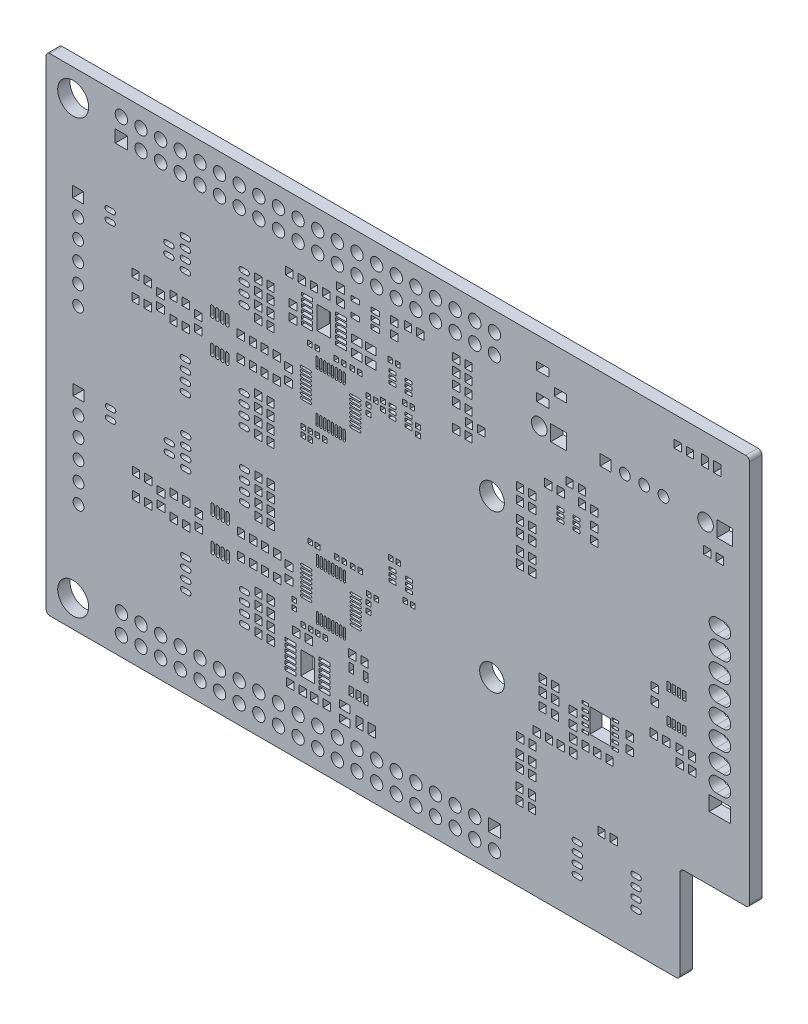
SolidWorks part; units mm, degrees
ref_plane "Plan de face" through (0, 0, 0) normal (0, 0, 1) x (1, 0, 0)
ref_plane "Plan de dessus" through (0, 0, 0) normal (0, 1, 0) x (1, 0, 0)
ref_plane "Plan de droite" through (0, 0, 0) normal (1, 0, 0) x (0, 0, -1)
sketch "Model" plane through (0, 0, 0) normal (0, 0, 1) x (1, 0, 0)
  line L0 (70.165, 24.645) -> (69.315, 24.645)
  line L1 (69.315, 24.645) -> (69.315, 24.995)
  line L2 (69.315, 24.995) -> (70.165, 24.995)
  line L3 (70.165, 24.995) -> (70.165, 24.645)
  line L4 (70.165, 23.845) -> (69.315, 23.845)
  line L5 (69.315, 23.845) -> (69.315, 24.195)
  line L6 (69.315, 24.195) -> (70.165, 24.195)
  line L7 (70.165, 24.195) -> (70.165, 23.845)
  line L8 (70.165, 23.045) -> (69.315, 23.045)
  line L9 (69.315, 23.045) -> (69.315, 23.395)
  line L10 (69.315, 23.395) -> (70.165, 23.395)
  line L11 (70.165, 23.395) -> (70.165, 23.045)
  line L12 (70.165, 22.245) -> (69.315, 22.245)
  line L13 (69.315, 22.245) -> (69.315, 22.595)
  line L14 (69.315, 22.595) -> (70.165, 22.595)
  line L15 (70.165, 22.595) -> (70.165, 22.245)
  line L16 (70.165, 21.445) -> (69.315, 21.445)
  line L17 (69.315, 21.445) -> (69.315, 21.795)
  line L18 (69.315, 21.795) -> (70.165, 21.795)
  line L19 (70.165, 21.795) -> (70.165, 21.445)
  line L20 (74.065, 21.445) -> (73.215, 21.445)
  line L21 (73.215, 21.445) -> (73.215, 21.795)
  line L22 (73.215, 21.795) -> (74.065, 21.795)
  line L23 (74.065, 21.795) -> (74.065, 21.445)
  line L24 (74.065, 22.245) -> (73.215, 22.245)
  line L25 (73.215, 22.245) -> (73.215, 22.595)
  line L26 (73.215, 22.595) -> (74.065, 22.595)
  line L27 (74.065, 22.595) -> (74.065, 22.245)
  line L28 (74.065, 23.045) -> (73.215, 23.045)
  line L29 (73.215, 23.045) -> (73.215, 23.395)
  line L30 (73.215, 23.395) -> (74.065, 23.395)
  line L31 (74.065, 23.395) -> (74.065, 23.045)
  line L32 (74.065, 23.845) -> (73.215, 23.845)
  line L33 (73.215, 23.845) -> (73.215, 24.195)
  line L34 (73.215, 24.195) -> (74.065, 24.195)
  line L35 (74.065, 24.195) -> (74.065, 23.845)
  line L36 (74.065, 24.645) -> (73.215, 24.645)
  line L37 (73.215, 24.645) -> (73.215, 24.995)
  line L38 (73.215, 24.995) -> (74.065, 24.995)
  line L39 (74.065, 24.995) -> (74.065, 24.645)
  line L40 (73.04, 24.77) -> (73.04, 21.67)
  line L41 (73.04, 21.67) -> (70.34, 21.67)
  line L42 (70.34, 21.67) -> (70.34, 24.77)
  line L43 (70.34, 24.77) -> (73.04, 24.77)
  line L44 (82.3, 31.54) -> (82.3, 32.64)
  line L45 (82.3, 32.64) -> (82.75, 32.64)
  line L46 (82.75, 32.64) -> (82.75, 31.54)
  line L47 (82.75, 31.54) -> (82.3, 31.54)
  line L48 (81.65, 31.54) -> (81.65, 32.64)
  line L49 (81.65, 32.64) -> (82.1, 32.64)
  line L50 (82.1, 32.64) -> (82.1, 31.54)
  line L51 (82.1, 31.54) -> (81.65, 31.54)
  line L52 (81, 31.54) -> (81, 32.64)
  line L53 (81, 32.64) -> (81.45, 32.64)
  line L54 (81.45, 32.64) -> (81.45, 31.54)
  line L55 (81.45, 31.54) -> (81, 31.54)
  line L56 (80.35, 31.54) -> (80.35, 32.64)
  line L57 (80.35, 32.64) -> (80.8, 32.64)
  line L58 (80.8, 32.64) -> (80.8, 31.54)
  line L59 (80.8, 31.54) -> (80.35, 31.54)
  line L60 (80.35, 27.64) -> (80.35, 28.74)
  line L61 (80.35, 28.74) -> (80.8, 28.74)
  line L62 (80.8, 28.74) -> (80.8, 27.64)
  line L63 (80.8, 27.64) -> (80.35, 27.64)
  line L64 (81, 27.64) -> (81, 28.74)
  line L65 (81, 28.74) -> (81.45, 28.74)
  line L66 (81.45, 28.74) -> (81.45, 27.64)
  line L67 (81.45, 27.64) -> (81, 27.64)
  line L68 (81.65, 27.64) -> (81.65, 28.74)
  line L69 (81.65, 28.74) -> (82.1, 28.74)
  line L70 (82.1, 28.74) -> (82.1, 27.64)
  line L71 (82.1, 27.64) -> (81.65, 27.64)
  line L72 (82.3, 27.64) -> (82.3, 28.74)
  line L73 (82.3, 28.74) -> (82.75, 28.74)
  line L74 (82.75, 28.74) -> (82.75, 27.64)
  line L75 (82.75, 27.64) -> (82.3, 27.64)
  line L76 (88.567, 20.7375) -> (85.773, 20.7375)
  line L77 (85.773, 20.7375) -> (85.773, 22.6425)
  line L78 (85.773, 22.6425) -> (88.567, 22.6425)
  line L79 (88.567, 22.6425) -> (88.567, 20.7375)
  line L80 (86.7255, 25.1825) -> (87.6145, 25.1825)
  line L81 (87.6145, 23.2775) -> (86.7255, 23.2775)
  line L82 (86.7255, 27.7225) -> (87.6145, 27.7225)
  line L83 (87.6145, 25.8175) -> (86.7255, 25.8175)
  line L84 (86.7255, 30.2625) -> (87.6145, 30.2625)
  line L85 (87.6145, 28.3575) -> (86.7255, 28.3575)
  line L86 (86.7255, 32.8025) -> (87.6145, 32.8025)
  line L87 (87.6145, 30.8975) -> (86.7255, 30.8975)
  line L88 (86.7255, 35.3425) -> (87.6145, 35.3425)
  line L89 (87.6145, 33.4375) -> (86.7255, 33.4375)
  line L90 (86.7255, 37.8825) -> (87.6145, 37.8825)
  line L91 (87.6145, 35.9775) -> (86.7255, 35.9775)
  line L92 (86.7255, 40.4225) -> (87.6145, 40.4225)
  line L93 (87.6145, 38.5175) -> (86.7255, 38.5175)
  line L94 (86.7255, 42.9625) -> (87.6145, 42.9625)
  line L95 (87.6145, 41.0575) -> (86.7255, 41.0575)
  line L96 (63.4437, 60.0107) -> (65.0437, 60.0107)
  line L97 (65.0437, 60.0107) -> (65.0437, 59.0107)
  line L98 (65.0437, 59.0107) -> (63.4437, 59.0107)
  line L99 (63.4437, 59.0107) -> (63.4437, 60.0107)
  line L100 (65.7437, 58.2607) -> (67.3437, 58.2607)
  line L101 (67.3437, 58.2607) -> (67.3437, 57.2607)
  line L102 (67.3437, 57.2607) -> (65.7437, 57.2607)
  line L103 (65.7437, 57.2607) -> (65.7437, 58.2607)
  line L104 (63.4537, 56.5107) -> (65.0537, 56.5107)
  line L105 (65.0537, 56.5107) -> (65.0537, 55.5107)
  line L106 (65.0537, 55.5107) -> (63.4537, 55.5107)
  line L107 (63.4537, 55.5107) -> (63.4537, 56.5107)
  line L108 (32.3305, 12.39) -> (30.9055, 12.39)
  line L109 (30.9055, 12.39) -> (30.9055, 12.84)
  line L110 (30.9055, 12.84) -> (32.3305, 12.84)
  line L111 (32.3305, 12.84) -> (32.3305, 12.39)
  line L112 (32.3305, 11.74) -> (30.9055, 11.74)
  line L113 (30.9055, 11.74) -> (30.9055, 12.19)
  line L114 (30.9055, 12.19) -> (32.3305, 12.19)
  line L115 (32.3305, 12.19) -> (32.3305, 11.74)
  line L116 (32.3305, 11.09) -> (30.9055, 11.09)
  line L117 (30.9055, 11.09) -> (30.9055, 11.54)
  line L118 (30.9055, 11.54) -> (32.3305, 11.54)
  line L119 (32.3305, 11.54) -> (32.3305, 11.09)
  line L120 (32.3305, 10.44) -> (30.9055, 10.44)
  line L121 (30.9055, 10.44) -> (30.9055, 10.89)
  line L122 (30.9055, 10.89) -> (32.3305, 10.89)
  line L123 (32.3305, 10.89) -> (32.3305, 10.44)
  line L124 (32.3305, 9.79) -> (30.9055, 9.79)
  line L125 (30.9055, 9.79) -> (30.9055, 10.24)
  line L126 (30.9055, 10.24) -> (32.3305, 10.24)
  line L127 (32.3305, 10.24) -> (32.3305, 9.79)
  line L128 (32.3305, 9.14) -> (30.9055, 9.14)
  line L129 (30.9055, 9.14) -> (30.9055, 9.59)
  line L130 (30.9055, 9.59) -> (32.3305, 9.59)
  line L131 (32.3305, 9.59) -> (32.3305, 9.14)
  line L132 (36.7545, 9.14) -> (35.3295, 9.14)
  line L133 (35.3295, 9.14) -> (35.3295, 9.59)
  line L134 (35.3295, 9.59) -> (36.7545, 9.59)
  line L135 (36.7545, 9.59) -> (36.7545, 9.14)
  line L136 (36.7545, 9.79) -> (35.3295, 9.79)
  line L137 (35.3295, 9.79) -> (35.3295, 10.24)
  line L138 (35.3295, 10.24) -> (36.7545, 10.24)
  line L139 (36.7545, 10.24) -> (36.7545, 9.79)
  line L140 (36.7545, 10.44) -> (35.3295, 10.44)
  line L141 (35.3295, 10.44) -> (35.3295, 10.89)
  line L142 (35.3295, 10.89) -> (36.7545, 10.89)
  line L143 (36.7545, 10.89) -> (36.7545, 10.44)
  line L144 (36.7545, 11.09) -> (35.3295, 11.09)
  line L145 (35.3295, 11.09) -> (35.3295, 11.54)
  line L146 (35.3295, 11.54) -> (36.7545, 11.54)
  line L147 (36.7545, 11.54) -> (36.7545, 11.09)
  line L148 (36.7545, 11.74) -> (35.3295, 11.74)
  line L149 (35.3295, 11.74) -> (35.3295, 12.19)
  line L150 (35.3295, 12.19) -> (36.7545, 12.19)
  line L151 (36.7545, 12.19) -> (36.7545, 11.74)
  line L152 (36.7545, 12.39) -> (35.3295, 12.39)
  line L153 (35.3295, 12.39) -> (35.3295, 12.84)
  line L154 (35.3295, 12.84) -> (36.7545, 12.84)
  line L155 (36.7545, 12.84) -> (36.7545, 12.39)
  line L156 (34.7065, 12.4635) -> (34.7065, 9.5165)
  line L157 (34.7065, 9.5165) -> (32.9535, 9.5165)
  line L158 (32.9535, 9.5165) -> (32.9535, 12.4635)
  line L159 (32.9535, 12.4635) -> (34.7065, 12.4635)
  line L160 (37.4395, 49.32) -> (38.8645, 49.32)
  line L161 (38.8645, 49.32) -> (38.8645, 48.87)
  line L162 (38.8645, 48.87) -> (37.4395, 48.87)
  line L163 (37.4395, 48.87) -> (37.4395, 49.32)
  line L164 (37.4395, 49.97) -> (38.8645, 49.97)
  line L165 (38.8645, 49.97) -> (38.8645, 49.52)
  line L166 (38.8645, 49.52) -> (37.4395, 49.52)
  line L167 (37.4395, 49.52) -> (37.4395, 49.97)
  line L168 (37.4395, 50.62) -> (38.8645, 50.62)
  line L169 (38.8645, 50.62) -> (38.8645, 50.17)
  line L170 (38.8645, 50.17) -> (37.4395, 50.17)
  line L171 (37.4395, 50.17) -> (37.4395, 50.62)
  line L172 (37.4395, 51.27) -> (38.8645, 51.27)
  line L173 (38.8645, 51.27) -> (38.8645, 50.82)
  line L174 (38.8645, 50.82) -> (37.4395, 50.82)
  line L175 (37.4395, 50.82) -> (37.4395, 51.27)
  line L176 (37.4395, 51.92) -> (38.8645, 51.92)
  line L177 (38.8645, 51.92) -> (38.8645, 51.47)
  line L178 (38.8645, 51.47) -> (37.4395, 51.47)
  line L179 (37.4395, 51.47) -> (37.4395, 51.92)
  line L180 (37.4395, 52.57) -> (38.8645, 52.57)
  line L181 (38.8645, 52.57) -> (38.8645, 52.12)
  line L182 (38.8645, 52.12) -> (37.4395, 52.12)
  line L183 (37.4395, 52.12) -> (37.4395, 52.57)
  line L184 (33.0155, 52.57) -> (34.4405, 52.57)
  line L185 (34.4405, 52.57) -> (34.4405, 52.12)
  line L186 (34.4405, 52.12) -> (33.0155, 52.12)
  line L187 (33.0155, 52.12) -> (33.0155, 52.57)
  line L188 (33.0155, 51.92) -> (34.4405, 51.92)
  line L189 (34.4405, 51.92) -> (34.4405, 51.47)
  line L190 (34.4405, 51.47) -> (33.0155, 51.47)
  line L191 (33.0155, 51.47) -> (33.0155, 51.92)
  line L192 (33.0155, 51.27) -> (34.4405, 51.27)
  line L193 (34.4405, 51.27) -> (34.4405, 50.82)
  line L194 (34.4405, 50.82) -> (33.0155, 50.82)
  line L195 (33.0155, 50.82) -> (33.0155, 51.27)
  line L196 (33.0155, 50.62) -> (34.4405, 50.62)
  line L197 (34.4405, 50.62) -> (34.4405, 50.17)
  line L198 (34.4405, 50.17) -> (33.0155, 50.17)
  line L199 (33.0155, 50.17) -> (33.0155, 50.62)
  line L200 (33.0155, 49.97) -> (34.4405, 49.97)
  line L201 (34.4405, 49.97) -> (34.4405, 49.52)
  line L202 (34.4405, 49.52) -> (33.0155, 49.52)
  line L203 (33.0155, 49.52) -> (33.0155, 49.97)
  line L204 (33.0155, 49.32) -> (34.4405, 49.32)
  line L205 (34.4405, 49.32) -> (34.4405, 48.87)
  line L206 (34.4405, 48.87) -> (33.0155, 48.87)
  line L207 (33.0155, 48.87) -> (33.0155, 49.32)
  line L208 (35.0635, 49.2465) -> (35.0635, 52.1935)
  line L209 (35.0635, 52.1935) -> (36.8165, 52.1935)
  line L210 (36.8165, 52.1935) -> (36.8165, 49.2465)
  line L211 (36.8165, 49.2465) -> (35.0635, 49.2465)
  line L212 (39.7669, 10.4724) -> (39.1669, 10.4724)
  line L213 (39.1669, 10.4724) -> (39.1669, 11.5724)
  line L214 (39.1669, 11.5724) -> (39.7669, 11.5724)
  line L215 (39.7669, 11.5724) -> (39.7669, 10.4724)
  line L216 (40.7169, 10.4724) -> (40.1169, 10.4724)
  line L217 (40.1169, 10.4724) -> (40.1169, 11.5724)
  line L218 (40.1169, 11.5724) -> (40.7169, 11.5724)
  line L219 (40.7169, 11.5724) -> (40.7169, 10.4724)
  line L220 (41.6669, 10.4724) -> (41.0669, 10.4724)
  line L221 (41.0669, 10.4724) -> (41.0669, 11.5724)
  line L222 (41.0669, 11.5724) -> (41.6669, 11.5724)
  line L223 (41.6669, 11.5724) -> (41.6669, 10.4724)
  line L224 (41.6669, 13.0724) -> (41.0669, 13.0724)
  line L225 (41.0669, 13.0724) -> (41.0669, 14.1724)
  line L226 (41.0669, 14.1724) -> (41.6669, 14.1724)
  line L227 (41.6669, 14.1724) -> (41.6669, 13.0724)
  line L228 (39.7669, 13.0724) -> (39.1669, 13.0724)
  line L229 (39.1669, 13.0724) -> (39.1669, 14.1724)
  line L230 (39.1669, 14.1724) -> (39.7669, 14.1724)
  line L231 (39.7669, 14.1724) -> (39.7669, 13.0724)
  line L232 (43.12, 53.52) -> (43.12, 52.92)
  line L233 (43.12, 52.92) -> (42.02, 52.92)
  line L234 (42.02, 52.92) -> (42.02, 53.52)
  line L235 (42.02, 53.52) -> (43.12, 53.52)
  line L236 (43.12, 54.47) -> (43.12, 53.87)
  line L237 (43.12, 53.87) -> (42.02, 53.87)
  line L238 (42.02, 53.87) -> (42.02, 54.47)
  line L239 (42.02, 54.47) -> (43.12, 54.47)
  line L240 (43.12, 55.42) -> (43.12, 54.82)
  line L241 (43.12, 54.82) -> (42.02, 54.82)
  line L242 (42.02, 54.82) -> (42.02, 55.42)
  line L243 (42.02, 55.42) -> (43.12, 55.42)
  line L244 (40.52, 55.42) -> (40.52, 54.82)
  line L245 (40.52, 54.82) -> (39.42, 54.82)
  line L246 (39.42, 54.82) -> (39.42, 55.42)
  line L247 (39.42, 55.42) -> (40.52, 55.42)
  line L248 (40.52, 53.52) -> (40.52, 52.92)
  line L249 (40.52, 52.92) -> (39.42, 52.92)
  line L250 (39.42, 52.92) -> (39.42, 53.52)
  line L251 (39.42, 53.52) -> (40.52, 53.52)
  line L252 (18.42, 15.04) -> (17.72, 15.04)
  line L253 (17.72, 15.69) -> (18.42, 15.69)
  line L254 (18.42, 13.77) -> (17.72, 13.77)
  line L255 (17.72, 14.42) -> (18.42, 14.42)
  line L256 (18.42, 12.5) -> (17.72, 12.5)
  line L257 (17.72, 13.15) -> (18.42, 13.15)
  line L258 (18.42, 11.23) -> (17.72, 11.23)
  line L259 (17.72, 11.88) -> (18.42, 11.88)
  line L260 (26.02, 11.23) -> (25.32, 11.23)
  line L261 (25.32, 11.88) -> (26.02, 11.88)
  line L262 (26.02, 12.5) -> (25.32, 12.5)
  line L263 (25.32, 13.15) -> (26.02, 13.15)
  line L264 (26.02, 13.77) -> (25.32, 13.77)
  line L265 (25.32, 14.42) -> (26.02, 14.42)
  line L266 (26.02, 15.04) -> (25.32, 15.04)
  line L267 (25.32, 15.69) -> (26.02, 15.69)
  line L268 (18.42, 28.7) -> (17.72, 28.7)
  line L269 (17.72, 29.35) -> (18.42, 29.35)
  line L270 (18.42, 27.43) -> (17.72, 27.43)
  line L271 (17.72, 28.08) -> (18.42, 28.08)
  line L272 (18.42, 26.16) -> (17.72, 26.16)
  line L273 (17.72, 26.81) -> (18.42, 26.81)
  line L274 (18.42, 24.89) -> (17.72, 24.89)
  line L275 (17.72, 25.54) -> (18.42, 25.54)
  line L276 (26.02, 24.89) -> (25.32, 24.89)
  line L277 (25.32, 25.54) -> (26.02, 25.54)
  line L278 (26.02, 26.16) -> (25.32, 26.16)
  line L279 (25.32, 26.81) -> (26.02, 26.81)
  line L280 (26.02, 27.43) -> (25.32, 27.43)
  line L281 (25.32, 28.08) -> (26.02, 28.08)
  line L282 (26.02, 28.7) -> (25.32, 28.7)
  line L283 (25.32, 29.35) -> (26.02, 29.35)
  line L284 (18.37, 37.21) -> (17.67, 37.21)
  line L285 (17.67, 37.86) -> (18.37, 37.86)
  line L286 (18.37, 35.94) -> (17.67, 35.94)
  line L287 (17.67, 36.59) -> (18.37, 36.59)
  line L288 (18.37, 34.67) -> (17.67, 34.67)
  line L289 (17.67, 35.32) -> (18.37, 35.32)
  line L290 (18.37, 33.4) -> (17.67, 33.4)
  line L291 (17.67, 34.05) -> (18.37, 34.05)
  line L292 (25.97, 33.4) -> (25.27, 33.4)
  line L293 (25.27, 34.05) -> (25.97, 34.05)
  line L294 (25.97, 34.67) -> (25.27, 34.67)
  line L295 (25.27, 35.32) -> (25.97, 35.32)
  line L296 (25.97, 35.94) -> (25.27, 35.94)
  line L297 (25.27, 36.59) -> (25.97, 36.59)
  line L298 (25.97, 37.21) -> (25.27, 37.21)
  line L299 (25.27, 37.86) -> (25.97, 37.86)
  line L300 (18.37, 50.87) -> (17.67, 50.87)
  line L301 (17.67, 51.52) -> (18.37, 51.52)
  line L302 (18.37, 49.6) -> (17.67, 49.6)
  line L303 (17.67, 50.25) -> (18.37, 50.25)
  line L304 (18.37, 48.33) -> (17.67, 48.33)
  line L305 (17.67, 48.98) -> (18.37, 48.98)
  line L306 (18.37, 47.06) -> (17.67, 47.06)
  line L307 (17.67, 47.71) -> (18.37, 47.71)
  line L308 (25.97, 47.06) -> (25.27, 47.06)
  line L309 (25.27, 47.71) -> (25.97, 47.71)
  line L310 (25.97, 48.33) -> (25.27, 48.33)
  line L311 (25.27, 48.98) -> (25.97, 48.98)
  line L312 (25.97, 49.6) -> (25.27, 49.6)
  line L313 (25.27, 50.25) -> (25.97, 50.25)
  line L314 (25.97, 50.87) -> (25.27, 50.87)
  line L315 (25.27, 51.52) -> (25.97, 51.52)
  line L316 (69.07, 8.46) -> (68.37, 8.46)
  line L317 (68.37, 9.11) -> (69.07, 9.11)
  line L318 (69.07, 7.19) -> (68.37, 7.19)
  line L319 (68.37, 7.84) -> (69.07, 7.84)
  line L320 (69.07, 5.92) -> (68.37, 5.92)
  line L321 (68.37, 6.57) -> (69.07, 6.57)
  line L322 (69.07, 4.65) -> (68.37, 4.65)
  line L323 (68.37, 5.3) -> (69.07, 5.3)
  line L324 (76.67, 4.65) -> (75.97, 4.65)
  line L325 (75.97, 5.3) -> (76.67, 5.3)
  line L326 (76.67, 5.92) -> (75.97, 5.92)
  line L327 (75.97, 6.57) -> (76.67, 6.57)
  line L328 (76.67, 7.19) -> (75.97, 7.19)
  line L329 (75.97, 7.84) -> (76.67, 7.84)
  line L330 (76.67, 8.46) -> (75.97, 8.46)
  line L331 (75.97, 9.11) -> (76.67, 9.11)
  line L332 (34.225, 21.88) -> (33.075, 21.88)
  line L333 (33.075, 22.18) -> (34.225, 22.18)
  line L334 (34.225, 21.38) -> (33.075, 21.38)
  line L335 (33.075, 21.68) -> (34.225, 21.68)
  line L336 (34.225, 20.88) -> (33.075, 20.88)
  line L337 (33.075, 21.18) -> (34.225, 21.18)
  line L338 (34.225, 20.38) -> (33.075, 20.38)
  line L339 (33.075, 20.68) -> (34.225, 20.68)
  line L340 (34.225, 19.88) -> (33.075, 19.88)
  line L341 (33.075, 20.18) -> (34.225, 20.18)
  line L342 (34.225, 19.38) -> (33.075, 19.38)
  line L343 (33.075, 19.68) -> (34.225, 19.68)
  line L344 (34.225, 18.88) -> (33.075, 18.88)
  line L345 (33.075, 19.18) -> (34.225, 19.18)
  line L346 (34.225, 18.38) -> (33.075, 18.38)
  line L347 (33.075, 18.68) -> (34.225, 18.68)
  line L348 (35.25, 17.655) -> (35.25, 16.505)
  line L349 (34.95, 16.505) -> (34.95, 17.655)
  line L350 (35.75, 17.655) -> (35.75, 16.505)
  line L351 (35.45, 16.505) -> (35.45, 17.655)
  line L352 (36.25, 17.655) -> (36.25, 16.505)
  line L353 (35.95, 16.505) -> (35.95, 17.655)
  line L354 (36.75, 17.655) -> (36.75, 16.505)
  line L355 (36.45, 16.505) -> (36.45, 17.655)
  line L356 (37.25, 17.655) -> (37.25, 16.505)
  line L357 (36.95, 16.505) -> (36.95, 17.655)
  line L358 (37.75, 17.655) -> (37.75, 16.505)
  line L359 (37.45, 16.505) -> (37.45, 17.655)
  line L360 (38.25, 17.655) -> (38.25, 16.505)
  line L361 (37.95, 16.505) -> (37.95, 17.655)
  line L362 (38.75, 17.655) -> (38.75, 16.505)
  line L363 (38.45, 16.505) -> (38.45, 17.655)
  line L364 (40.625, 18.38) -> (39.475, 18.38)
  line L365 (39.475, 18.68) -> (40.625, 18.68)
  line L366 (40.625, 18.88) -> (39.475, 18.88)
  line L367 (39.475, 19.18) -> (40.625, 19.18)
  line L368 (40.625, 19.38) -> (39.475, 19.38)
  line L369 (39.475, 19.68) -> (40.625, 19.68)
  line L370 (40.625, 19.88) -> (39.475, 19.88)
  line L371 (39.475, 20.18) -> (40.625, 20.18)
  line L372 (40.625, 20.38) -> (39.475, 20.38)
  line L373 (39.475, 20.68) -> (40.625, 20.68)
  line L374 (40.625, 20.88) -> (39.475, 20.88)
  line L375 (39.475, 21.18) -> (40.625, 21.18)
  line L376 (40.625, 21.38) -> (39.475, 21.38)
  line L377 (39.475, 21.68) -> (40.625, 21.68)
  line L378 (40.625, 21.88) -> (39.475, 21.88)
  line L379 (39.475, 22.18) -> (40.625, 22.18)
  line L380 (38.75, 24.055) -> (38.75, 22.905)
  line L381 (38.45, 22.905) -> (38.45, 24.055)
  line L382 (38.25, 24.055) -> (38.25, 22.905)
  line L383 (37.95, 22.905) -> (37.95, 24.055)
  line L384 (37.75, 24.055) -> (37.75, 22.905)
  line L385 (37.45, 22.905) -> (37.45, 24.055)
  line L386 (37.25, 24.055) -> (37.25, 22.905)
  line L387 (36.95, 22.905) -> (36.95, 24.055)
  line L388 (36.75, 24.055) -> (36.75, 22.905)
  line L389 (36.45, 22.905) -> (36.45, 24.055)
  line L390 (36.25, 24.055) -> (36.25, 22.905)
  line L391 (35.95, 22.905) -> (35.95, 24.055)
  line L392 (35.75, 24.055) -> (35.75, 22.905)
  line L393 (35.45, 22.905) -> (35.45, 24.055)
  line L394 (35.25, 24.055) -> (35.25, 22.905)
  line L395 (34.95, 22.905) -> (34.95, 24.055)
  line L396 (34.175, 44.05) -> (33.025, 44.05)
  line L397 (33.025, 44.35) -> (34.175, 44.35)
  line L398 (34.175, 43.55) -> (33.025, 43.55)
  line L399 (33.025, 43.85) -> (34.175, 43.85)
  line L400 (34.175, 43.05) -> (33.025, 43.05)
  line L401 (33.025, 43.35) -> (34.175, 43.35)
  line L402 (34.175, 42.55) -> (33.025, 42.55)
  line L403 (33.025, 42.85) -> (34.175, 42.85)
  line L404 (34.175, 42.05) -> (33.025, 42.05)
  line L405 (33.025, 42.35) -> (34.175, 42.35)
  line L406 (34.175, 41.55) -> (33.025, 41.55)
  line L407 (33.025, 41.85) -> (34.175, 41.85)
  line L408 (34.175, 41.05) -> (33.025, 41.05)
  line L409 (33.025, 41.35) -> (34.175, 41.35)
  line L410 (34.175, 40.55) -> (33.025, 40.55)
  line L411 (33.025, 40.85) -> (34.175, 40.85)
  line L412 (35.2, 39.825) -> (35.2, 38.675)
  line L413 (34.9, 38.675) -> (34.9, 39.825)
  line L414 (35.7, 39.825) -> (35.7, 38.675)
  line L415 (35.4, 38.675) -> (35.4, 39.825)
  line L416 (36.2, 39.825) -> (36.2, 38.675)
  line L417 (35.9, 38.675) -> (35.9, 39.825)
  line L418 (36.7, 39.825) -> (36.7, 38.675)
  line L419 (36.4, 38.675) -> (36.4, 39.825)
  line L420 (37.2, 39.825) -> (37.2, 38.675)
  line L421 (36.9, 38.675) -> (36.9, 39.825)
  line L422 (37.7, 39.825) -> (37.7, 38.675)
  line L423 (37.4, 38.675) -> (37.4, 39.825)
  line L424 (38.2, 39.825) -> (38.2, 38.675)
  line L425 (37.9, 38.675) -> (37.9, 39.825)
  line L426 (38.7, 39.825) -> (38.7, 38.675)
  line L427 (38.4, 38.675) -> (38.4, 39.825)
  line L428 (40.575, 40.55) -> (39.425, 40.55)
  line L429 (39.425, 40.85) -> (40.575, 40.85)
  line L430 (40.575, 41.05) -> (39.425, 41.05)
  line L431 (39.425, 41.35) -> (40.575, 41.35)
  line L432 (40.575, 41.55) -> (39.425, 41.55)
  line L433 (39.425, 41.85) -> (40.575, 41.85)
  line L434 (40.575, 42.05) -> (39.425, 42.05)
  line L435 (39.425, 42.35) -> (40.575, 42.35)
  line L436 (40.575, 42.55) -> (39.425, 42.55)
  line L437 (39.425, 42.85) -> (40.575, 42.85)
  line L438 (40.575, 43.05) -> (39.425, 43.05)
  line L439 (39.425, 43.35) -> (40.575, 43.35)
  line L440 (40.575, 43.55) -> (39.425, 43.55)
  line L441 (39.425, 43.85) -> (40.575, 43.85)
  line L442 (40.575, 44.05) -> (39.425, 44.05)
  line L443 (39.425, 44.35) -> (40.575, 44.35)
  line L444 (38.7, 46.225) -> (38.7, 45.075)
  line L445 (38.4, 45.075) -> (38.4, 46.225)
  line L446 (38.2, 46.225) -> (38.2, 45.075)
  line L447 (37.9, 45.075) -> (37.9, 46.225)
  line L448 (37.7, 46.225) -> (37.7, 45.075)
  line L449 (37.4, 45.075) -> (37.4, 46.225)
  line L450 (37.2, 46.225) -> (37.2, 45.075)
  line L451 (36.9, 45.075) -> (36.9, 46.225)
  line L452 (36.7, 46.225) -> (36.7, 45.075)
  line L453 (36.4, 45.075) -> (36.4, 46.225)
  line L454 (36.2, 46.225) -> (36.2, 45.075)
  line L455 (35.9, 45.075) -> (35.9, 46.225)
  line L456 (35.7, 46.225) -> (35.7, 45.075)
  line L457 (35.4, 45.075) -> (35.4, 46.225)
  line L458 (35.2, 46.225) -> (35.2, 45.075)
  line L459 (34.9, 45.075) -> (34.9, 46.225)
  line L460 (21.76, 18.655) -> (21.76, 17.605)
  line L461 (21.31, 17.605) -> (21.31, 18.655)
  line L462 (22.41, 18.655) -> (22.41, 17.605)
  line L463 (21.96, 17.605) -> (21.96, 18.655)
  line L464 (23.06, 18.655) -> (23.06, 17.605)
  line L465 (22.61, 17.605) -> (22.61, 18.655)
  line L466 (23.71, 18.655) -> (23.71, 17.605)
  line L467 (23.26, 17.605) -> (23.26, 18.655)
  line L468 (23.71, 22.955) -> (23.71, 21.905)
  line L469 (23.26, 21.905) -> (23.26, 22.955)
  line L470 (23.06, 22.955) -> (23.06, 21.905)
  line L471 (22.61, 21.905) -> (22.61, 22.955)
  line L472 (22.41, 22.955) -> (22.41, 21.905)
  line L473 (21.96, 21.905) -> (21.96, 22.955)
  line L474 (21.76, 22.955) -> (21.76, 21.905)
  line L475 (21.31, 21.905) -> (21.31, 22.955)
  line L476 (21.71, 40.825) -> (21.71, 39.775)
  line L477 (21.26, 39.775) -> (21.26, 40.825)
  line L478 (22.36, 40.825) -> (22.36, 39.775)
  line L479 (21.91, 39.775) -> (21.91, 40.825)
  line L480 (23.01, 40.825) -> (23.01, 39.775)
  line L481 (22.56, 39.775) -> (22.56, 40.825)
  line L482 (23.66, 40.825) -> (23.66, 39.775)
  line L483 (23.21, 39.775) -> (23.21, 40.825)
  line L484 (23.66, 45.125) -> (23.66, 44.075)
  line L485 (23.21, 44.075) -> (23.21, 45.125)
  line L486 (23.01, 45.125) -> (23.01, 44.075)
  line L487 (22.56, 44.075) -> (22.56, 45.125)
  line L488 (22.36, 45.125) -> (22.36, 44.075)
  line L489 (21.91, 44.075) -> (21.91, 45.125)
  line L490 (21.71, 45.125) -> (21.71, 44.075)
  line L491 (21.26, 44.075) -> (21.26, 45.125)
  line L492 (8.69, 26.85) -> (7.99, 26.85)
  line L493 (7.99, 27.5) -> (8.69, 27.5)
  line L494 (8.69, 25.58) -> (7.99, 25.58)
  line L495 (7.99, 26.23) -> (8.69, 26.23)
  line L496 (16.29, 25.58) -> (15.59, 25.58)
  line L497 (15.59, 26.23) -> (16.29, 26.23)
  line L498 (16.29, 26.85) -> (15.59, 26.85)
  line L499 (15.59, 27.5) -> (16.29, 27.5)
  line L500 (8.64, 49.02) -> (7.94, 49.02)
  line L501 (7.94, 49.67) -> (8.64, 49.67)
  line L502 (8.64, 47.75) -> (7.94, 47.75)
  line L503 (7.94, 48.4) -> (8.64, 48.4)
  line L504 (16.24, 47.75) -> (15.54, 47.75)
  line L505 (15.54, 48.4) -> (16.24, 48.4)
  line L506 (16.24, 49.02) -> (15.54, 49.02)
  line L507 (15.54, 49.67) -> (16.24, 49.67)
  line L508 (3.49, 27.55) -> (4.89, 27.55)
  line L509 (4.89, 27.55) -> (4.89, 26.15)
  line L510 (4.89, 26.15) -> (3.49, 26.15)
  line L511 (3.49, 26.15) -> (3.49, 27.55)
  line L512 (3.44, 49.72) -> (4.84, 49.72)
  line L513 (4.84, 49.72) -> (4.84, 48.32)
  line L514 (4.84, 48.32) -> (3.44, 48.32)
  line L515 (3.44, 48.32) -> (3.44, 49.72)
  line L516 (66.08, 44.77) -> (66.08, 45.17)
  line L517 (66.08, 45.17) -> (66.98, 45.17)
  line L518 (66.98, 45.17) -> (66.98, 44.77)
  line L519 (66.98, 44.77) -> (66.08, 44.77)
  line L520 (66.08, 44.12) -> (66.08, 44.52)
  line L521 (66.08, 44.52) -> (66.98, 44.52)
  line L522 (66.98, 44.52) -> (66.98, 44.12)
  line L523 (66.98, 44.12) -> (66.08, 44.12)
  line L524 (66.08, 43.47) -> (66.08, 43.87)
  line L525 (66.08, 43.87) -> (66.98, 43.87)
  line L526 (66.98, 43.87) -> (66.98, 43.47)
  line L527 (66.98, 43.47) -> (66.08, 43.47)
  line L528 (68.18, 43.47) -> (68.18, 43.87)
  line L529 (68.18, 43.87) -> (69.08, 43.87)
  line L530 (69.08, 43.87) -> (69.08, 43.47)
  line L531 (69.08, 43.47) -> (68.18, 43.47)
  line L532 (68.18, 44.12) -> (68.18, 44.52)
  line L533 (68.18, 44.52) -> (69.08, 44.52)
  line L534 (69.08, 44.52) -> (69.08, 44.12)
  line L535 (69.08, 44.12) -> (68.18, 44.12)
  line L536 (68.18, 44.77) -> (68.18, 45.17)
  line L537 (68.18, 45.17) -> (69.08, 45.17)
  line L538 (69.08, 45.17) -> (69.08, 44.77)
  line L539 (69.08, 44.77) -> (68.18, 44.77)
  line L540 (44.39, 27.09) -> (44.39, 27.49)
  line L541 (44.39, 27.49) -> (45.29, 27.49)
  line L542 (45.29, 27.49) -> (45.29, 27.09)
  line L543 (45.29, 27.09) -> (44.39, 27.09)
  line L544 (44.39, 26.44) -> (44.39, 26.84)
  line L545 (44.39, 26.84) -> (45.29, 26.84)
  line L546 (45.29, 26.84) -> (45.29, 26.44)
  line L547 (45.29, 26.44) -> (44.39, 26.44)
  line L548 (44.39, 25.79) -> (44.39, 26.19)
  line L549 (44.39, 26.19) -> (45.29, 26.19)
  line L550 (45.29, 26.19) -> (45.29, 25.79)
  line L551 (45.29, 25.79) -> (44.39, 25.79)
  line L552 (46.49, 25.79) -> (46.49, 26.19)
  line L553 (46.49, 26.19) -> (47.39, 26.19)
  line L554 (47.39, 26.19) -> (47.39, 25.79)
  line L555 (47.39, 25.79) -> (46.49, 25.79)
  line L556 (46.49, 26.44) -> (46.49, 26.84)
  line L557 (46.49, 26.84) -> (47.39, 26.84)
  line L558 (47.39, 26.84) -> (47.39, 26.44)
  line L559 (47.39, 26.44) -> (46.49, 26.44)
  line L560 (46.49, 27.09) -> (46.49, 27.49)
  line L561 (46.49, 27.49) -> (47.39, 27.49)
  line L562 (47.39, 27.49) -> (47.39, 27.09)
  line L563 (47.39, 27.09) -> (46.49, 27.09)
  line L564 (44.34, 49.26) -> (44.34, 49.66)
  line L565 (44.34, 49.66) -> (45.24, 49.66)
  line L566 (45.24, 49.66) -> (45.24, 49.26)
  line L567 (45.24, 49.26) -> (44.34, 49.26)
  line L568 (44.34, 48.61) -> (44.34, 49.01)
  line L569 (44.34, 49.01) -> (45.24, 49.01)
  line L570 (45.24, 49.01) -> (45.24, 48.61)
  line L571 (45.24, 48.61) -> (44.34, 48.61)
  line L572 (44.34, 47.96) -> (44.34, 48.36)
  line L573 (44.34, 48.36) -> (45.24, 48.36)
  line L574 (45.24, 48.36) -> (45.24, 47.96)
  line L575 (45.24, 47.96) -> (44.34, 47.96)
  line L576 (46.44, 47.96) -> (46.44, 48.36)
  line L577 (46.44, 48.36) -> (47.34, 48.36)
  line L578 (47.34, 48.36) -> (47.34, 47.96)
  line L579 (47.34, 47.96) -> (46.44, 47.96)
  line L580 (46.44, 48.61) -> (46.44, 49.01)
  line L581 (46.44, 49.01) -> (47.34, 49.01)
  line L582 (47.34, 49.01) -> (47.34, 48.61)
  line L583 (47.34, 48.61) -> (46.44, 48.61)
  line L584 (46.44, 49.26) -> (46.44, 49.66)
  line L585 (46.44, 49.66) -> (47.34, 49.66)
  line L586 (47.34, 49.66) -> (47.34, 49.26)
  line L587 (47.34, 49.26) -> (46.44, 49.26)
  line L588 (44.34, 45.44) -> (44.34, 45.84)
  line L589 (44.34, 45.84) -> (45.24, 45.84)
  line L590 (45.24, 45.84) -> (45.24, 45.44)
  line L591 (45.24, 45.44) -> (44.34, 45.44)
  line L592 (44.34, 44.79) -> (44.34, 45.19)
  line L593 (44.34, 45.19) -> (45.24, 45.19)
  line L594 (45.24, 45.19) -> (45.24, 44.79)
  line L595 (45.24, 44.79) -> (44.34, 44.79)
  line L596 (44.34, 44.14) -> (44.34, 44.54)
  line L597 (44.34, 44.54) -> (45.24, 44.54)
  line L598 (45.24, 44.54) -> (45.24, 44.14)
  line L599 (45.24, 44.14) -> (44.34, 44.14)
  line L600 (46.44, 44.14) -> (46.44, 44.54)
  line L601 (46.44, 44.54) -> (47.34, 44.54)
  line L602 (47.34, 44.54) -> (47.34, 44.14)
  line L603 (47.34, 44.14) -> (46.44, 44.14)
  line L604 (46.44, 44.79) -> (46.44, 45.19)
  line L605 (46.44, 45.19) -> (47.34, 45.19)
  line L606 (47.34, 45.19) -> (47.34, 44.79)
  line L607 (47.34, 44.79) -> (46.44, 44.79)
  line L608 (46.44, 45.44) -> (46.44, 45.84)
  line L609 (46.44, 45.84) -> (47.34, 45.84)
  line L610 (47.34, 45.84) -> (47.34, 45.44)
  line L611 (47.34, 45.44) -> (46.44, 45.44)
  line L612 (31.78, 17.315) -> (31.78, 17.905)
  line L613 (31.78, 17.905) -> (32.42, 17.905)
  line L614 (32.42, 17.905) -> (32.42, 17.315)
  line L615 (32.42, 17.315) -> (31.78, 17.315)
  line L616 (31.78, 16.355) -> (31.78, 16.945)
  line L617 (31.78, 16.945) -> (32.42, 16.945)
  line L618 (32.42, 16.945) -> (32.42, 16.355)
  line L619 (32.42, 16.355) -> (31.78, 16.355)
  line L620 (33.585, 15.05) -> (32.995, 15.05)
  line L621 (32.995, 15.05) -> (32.995, 15.69)
  line L622 (32.995, 15.69) -> (33.585, 15.69)
  line L623 (33.585, 15.69) -> (33.585, 15.05)
  line L624 (34.545, 15.05) -> (33.955, 15.05)
  line L625 (33.955, 15.05) -> (33.955, 15.69)
  line L626 (33.955, 15.69) -> (34.545, 15.69)
  line L627 (34.545, 15.69) -> (34.545, 15.05)
  line L628 (33.535, 36.28) -> (32.945, 36.28)
  line L629 (32.945, 36.28) -> (32.945, 36.92)
  line L630 (32.945, 36.92) -> (33.535, 36.92)
  line L631 (33.535, 36.92) -> (33.535, 36.28)
  line L632 (34.495, 36.28) -> (33.905, 36.28)
  line L633 (33.905, 36.28) -> (33.905, 36.92)
  line L634 (33.905, 36.92) -> (34.495, 36.92)
  line L635 (34.495, 36.92) -> (34.495, 36.28)
  line L636 (33.535, 37.22) -> (32.945, 37.22)
  line L637 (32.945, 37.22) -> (32.945, 37.86)
  line L638 (32.945, 37.86) -> (33.535, 37.86)
  line L639 (33.535, 37.86) -> (33.535, 37.22)
  line L640 (34.495, 37.22) -> (33.905, 37.22)
  line L641 (33.905, 37.22) -> (33.905, 37.86)
  line L642 (33.905, 37.86) -> (34.495, 37.86)
  line L643 (34.495, 37.86) -> (34.495, 37.22)
  line L644 (45.255, 28.83) -> (45.845, 28.83)
  line L645 (45.845, 28.83) -> (45.845, 28.19)
  line L646 (45.845, 28.19) -> (45.255, 28.19)
  line L647 (45.255, 28.19) -> (45.255, 28.83)
  line L648 (44.295, 28.83) -> (44.885, 28.83)
  line L649 (44.885, 28.83) -> (44.885, 28.19)
  line L650 (44.885, 28.19) -> (44.295, 28.19)
  line L651 (44.295, 28.19) -> (44.295, 28.83)
  line L652 (46.755, 24.34) -> (46.165, 24.34)
  line L653 (46.165, 24.34) -> (46.165, 24.98)
  line L654 (46.165, 24.98) -> (46.755, 24.98)
  line L655 (46.755, 24.98) -> (46.755, 24.34)
  line L656 (47.715, 24.34) -> (47.125, 24.34)
  line L657 (47.125, 24.34) -> (47.125, 24.98)
  line L658 (47.125, 24.98) -> (47.715, 24.98)
  line L659 (47.715, 24.98) -> (47.715, 24.34)
  line L660 (35.445, 15.05) -> (34.855, 15.05)
  line L661 (34.855, 15.05) -> (34.855, 15.69)
  line L662 (34.855, 15.69) -> (35.445, 15.69)
  line L663 (35.445, 15.69) -> (35.445, 15.05)
  line L664 (36.405, 15.05) -> (35.815, 15.05)
  line L665 (35.815, 15.05) -> (35.815, 15.69)
  line L666 (35.815, 15.69) -> (36.405, 15.69)
  line L667 (36.405, 15.69) -> (36.405, 15.05)
  line L668 (42.035, 22.71) -> (41.445, 22.71)
  line L669 (41.445, 22.71) -> (41.445, 23.35)
  line L670 (41.445, 23.35) -> (42.035, 23.35)
  line L671 (42.035, 23.35) -> (42.035, 22.71)
  line L672 (42.995, 22.71) -> (42.405, 22.71)
  line L673 (42.405, 22.71) -> (42.405, 23.35)
  line L674 (42.405, 23.35) -> (42.995, 23.35)
  line L675 (42.995, 23.35) -> (42.995, 22.71)
  line L676 (42.05, 21.375) -> (42.05, 20.785)
  line L677 (42.05, 20.785) -> (41.41, 20.785)
  line L678 (41.41, 20.785) -> (41.41, 21.375)
  line L679 (41.41, 21.375) -> (42.05, 21.375)
  line L680 (42.05, 22.335) -> (42.05, 21.745)
  line L681 (42.05, 21.745) -> (41.41, 21.745)
  line L682 (41.41, 21.745) -> (41.41, 22.335)
  line L683 (41.41, 22.335) -> (42.05, 22.335)
  line L684 (40.325, 25.44) -> (40.915, 25.44)
  line L685 (40.915, 25.44) -> (40.915, 24.8)
  line L686 (40.915, 24.8) -> (40.325, 24.8)
  line L687 (40.325, 24.8) -> (40.325, 25.44)
  line L688 (39.365, 25.44) -> (39.955, 25.44)
  line L689 (39.955, 25.44) -> (39.955, 24.8)
  line L690 (39.955, 24.8) -> (39.365, 24.8)
  line L691 (39.365, 24.8) -> (39.365, 25.44)
  line L692 (38.265, 25.45) -> (38.855, 25.45)
  line L693 (38.855, 25.45) -> (38.855, 24.81)
  line L694 (38.855, 24.81) -> (38.265, 24.81)
  line L695 (38.265, 24.81) -> (38.265, 25.45)
  line L696 (37.305, 25.45) -> (37.895, 25.45)
  line L697 (37.895, 25.45) -> (37.895, 24.81)
  line L698 (37.895, 24.81) -> (37.305, 24.81)
  line L699 (37.305, 24.81) -> (37.305, 25.45)
  line L700 (34.445, 24.8) -> (33.855, 24.8)
  line L701 (33.855, 24.8) -> (33.855, 25.44)
  line L702 (33.855, 25.44) -> (34.445, 25.44)
  line L703 (34.445, 25.44) -> (34.445, 24.8)
  line L704 (35.405, 24.8) -> (34.815, 24.8)
  line L705 (34.815, 24.8) -> (34.815, 25.44)
  line L706 (34.815, 25.44) -> (35.405, 25.44)
  line L707 (35.405, 25.44) -> (35.405, 24.8)
  line L708 (45.205, 51) -> (45.795, 51)
  line L709 (45.795, 51) -> (45.795, 50.36)
  line L710 (45.795, 50.36) -> (45.205, 50.36)
  line L711 (45.205, 50.36) -> (45.205, 51)
  line L712 (44.245, 51) -> (44.835, 51)
  line L713 (44.835, 51) -> (44.835, 50.36)
  line L714 (44.835, 50.36) -> (44.245, 50.36)
  line L715 (44.245, 50.36) -> (44.245, 51)
  line L716 (46.705, 46.51) -> (46.115, 46.51)
  line L717 (46.115, 46.51) -> (46.115, 47.15)
  line L718 (46.115, 47.15) -> (46.705, 47.15)
  line L719 (46.705, 47.15) -> (46.705, 46.51)
  line L720 (47.665, 46.51) -> (47.075, 46.51)
  line L721 (47.075, 46.51) -> (47.075, 47.15)
  line L722 (47.075, 47.15) -> (47.665, 47.15)
  line L723 (47.665, 47.15) -> (47.665, 46.51)
  line L724 (41.985, 44.88) -> (41.395, 44.88)
  line L725 (41.395, 44.88) -> (41.395, 45.52)
  line L726 (41.395, 45.52) -> (41.985, 45.52)
  line L727 (41.985, 45.52) -> (41.985, 44.88)
  line L728 (42.945, 44.88) -> (42.355, 44.88)
  line L729 (42.355, 44.88) -> (42.355, 45.52)
  line L730 (42.355, 45.52) -> (42.945, 45.52)
  line L731 (42.945, 45.52) -> (42.945, 44.88)
  line L732 (42, 43.545) -> (42, 42.955)
  line L733 (42, 42.955) -> (41.36, 42.955)
  line L734 (41.36, 42.955) -> (41.36, 43.545)
  line L735 (41.36, 43.545) -> (42, 43.545)
  line L736 (42, 44.505) -> (42, 43.915)
  line L737 (42, 43.915) -> (41.36, 43.915)
  line L738 (41.36, 43.915) -> (41.36, 44.505)
  line L739 (41.36, 44.505) -> (42, 44.505)
  line L740 (35.395, 37.22) -> (34.805, 37.22)
  line L741 (34.805, 37.22) -> (34.805, 37.86)
  line L742 (34.805, 37.86) -> (35.395, 37.86)
  line L743 (35.395, 37.86) -> (35.395, 37.22)
  line L744 (36.355, 37.22) -> (35.765, 37.22)
  line L745 (35.765, 37.22) -> (35.765, 37.86)
  line L746 (35.765, 37.86) -> (36.355, 37.86)
  line L747 (36.355, 37.86) -> (36.355, 37.22)
  line L748 (40.275, 47.61) -> (40.865, 47.61)
  line L749 (40.865, 47.61) -> (40.865, 46.97)
  line L750 (40.865, 46.97) -> (40.275, 46.97)
  line L751 (40.275, 46.97) -> (40.275, 47.61)
  line L752 (39.315, 47.61) -> (39.905, 47.61)
  line L753 (39.905, 47.61) -> (39.905, 46.97)
  line L754 (39.905, 46.97) -> (39.315, 46.97)
  line L755 (39.315, 46.97) -> (39.315, 47.61)
  line L756 (34.395, 46.97) -> (33.805, 46.97)
  line L757 (33.805, 46.97) -> (33.805, 47.61)
  line L758 (33.805, 47.61) -> (34.395, 47.61)
  line L759 (34.395, 47.61) -> (34.395, 46.97)
  line L760 (35.355, 46.97) -> (34.765, 46.97)
  line L761 (34.765, 46.97) -> (34.765, 47.61)
  line L762 (34.765, 47.61) -> (35.355, 47.61)
  line L763 (35.355, 47.61) -> (35.355, 46.97)
  line L764 (38.215, 47.62) -> (38.805, 47.62)
  line L765 (38.805, 47.62) -> (38.805, 46.98)
  line L766 (38.805, 46.98) -> (38.215, 46.98)
  line L767 (38.215, 46.98) -> (38.215, 47.62)
  line L768 (37.255, 47.62) -> (37.845, 47.62)
  line L769 (37.845, 47.62) -> (37.845, 46.98)
  line L770 (37.845, 46.98) -> (37.255, 46.98)
  line L771 (37.255, 46.98) -> (37.255, 47.62)
  line L772 (47.77, 44.745) -> (47.77, 45.335)
  line L773 (47.77, 45.335) -> (48.41, 45.335)
  line L774 (48.41, 45.335) -> (48.41, 44.745)
  line L775 (48.41, 44.745) -> (47.77, 44.745)
  line L776 (47.77, 43.785) -> (47.77, 44.375)
  line L777 (47.77, 44.375) -> (48.41, 44.375)
  line L778 (48.41, 44.375) -> (48.41, 43.785)
  line L779 (48.41, 43.785) -> (47.77, 43.785)
  line L780 (43.9, 44.955) -> (43.9, 44.365)
  line L781 (43.9, 44.365) -> (43.26, 44.365)
  line L782 (43.26, 44.365) -> (43.26, 44.955)
  line L783 (43.26, 44.955) -> (43.9, 44.955)
  line L784 (43.9, 45.915) -> (43.9, 45.325)
  line L785 (43.9, 45.325) -> (43.26, 45.325)
  line L786 (43.26, 45.325) -> (43.26, 45.915)
  line L787 (43.26, 45.915) -> (43.9, 45.915)
  line L788 (86.675, 50.2) -> (87.625, 50.2)
  line L789 (87.625, 50.2) -> (87.625, 49.2)
  line L790 (87.625, 49.2) -> (86.675, 49.2)
  line L791 (86.675, 49.2) -> (86.675, 50.2)
  line L792 (85.075, 50.2) -> (86.025, 50.2)
  line L793 (86.025, 50.2) -> (86.025, 49.2)
  line L794 (86.025, 49.2) -> (85.075, 49.2)
  line L795 (85.075, 49.2) -> (85.075, 50.2)
  line L796 (67.0537, 18.0001) -> (66.1037, 18.0001)
  line L797 (66.1037, 18.0001) -> (66.1037, 19.0001)
  line L798 (66.1037, 19.0001) -> (67.0537, 19.0001)
  line L799 (67.0537, 19.0001) -> (67.0537, 18.0001)
  line L800 (68.6537, 18.0001) -> (67.7037, 18.0001)
  line L801 (67.7037, 18.0001) -> (67.7037, 19.0001)
  line L802 (67.7037, 19.0001) -> (68.6537, 19.0001)
  line L803 (68.6537, 19.0001) -> (68.6537, 18.0001)
  line L804 (63.94, 17.9975) -> (62.99, 17.9975)
  line L805 (62.99, 17.9975) -> (62.99, 18.9975)
  line L806 (62.99, 18.9975) -> (63.94, 18.9975)
  line L807 (63.94, 18.9975) -> (63.94, 17.9975)
  line L808 (65.54, 17.9975) -> (64.59, 17.9975)
  line L809 (64.59, 17.9975) -> (64.59, 18.9975)
  line L810 (64.59, 18.9975) -> (65.54, 18.9975)
  line L811 (65.54, 18.9975) -> (65.54, 17.9975)
  line L812 (71.7587, 19.5525) -> (70.8087, 19.5525)
  line L813 (70.8087, 19.5525) -> (70.8087, 20.5525)
  line L814 (70.8087, 20.5525) -> (71.7587, 20.5525)
  line L815 (71.7587, 20.5525) -> (71.7587, 19.5525)
  line L816 (73.3587, 19.5525) -> (72.4087, 19.5525)
  line L817 (72.4087, 19.5525) -> (72.4087, 20.5525)
  line L818 (72.4087, 20.5525) -> (73.3587, 20.5525)
  line L819 (73.3587, 20.5525) -> (73.3587, 19.5525)
  line L820 (69.3028, 20.5524) -> (70.2528, 20.5524)
  line L821 (70.2528, 20.5524) -> (70.2528, 19.5524)
  line L822 (70.2528, 19.5524) -> (69.3028, 19.5524)
  line L823 (69.3028, 19.5524) -> (69.3028, 20.5524)
  line L824 (67.7028, 20.5524) -> (68.6528, 20.5524)
  line L825 (68.6528, 20.5524) -> (68.6528, 19.5524)
  line L826 (68.6528, 19.5524) -> (67.7028, 19.5524)
  line L827 (67.7028, 19.5524) -> (67.7028, 20.5524)
  line L828 (67.6778, 22.6828) -> (67.6778, 23.6328)
  line L829 (67.6778, 23.6328) -> (68.6778, 23.6328)
  line L830 (68.6778, 23.6328) -> (68.6778, 22.6828)
  line L831 (68.6778, 22.6828) -> (67.6778, 22.6828)
  line L832 (67.6778, 21.0828) -> (67.6778, 22.0328)
  line L833 (67.6778, 22.0328) -> (68.6778, 22.0328)
  line L834 (68.6778, 22.0328) -> (68.6778, 21.0828)
  line L835 (68.6778, 21.0828) -> (67.6778, 21.0828)
  line L836 (64.7024, 21.07) -> (63.7524, 21.07)
  line L837 (63.7524, 21.07) -> (63.7524, 22.07)
  line L838 (63.7524, 22.07) -> (64.7024, 22.07)
  line L839 (64.7024, 22.07) -> (64.7024, 21.07)
  line L840 (66.3024, 21.07) -> (65.3524, 21.07)
  line L841 (65.3524, 21.07) -> (65.3524, 22.07)
  line L842 (65.3524, 22.07) -> (66.3024, 22.07)
  line L843 (66.3024, 22.07) -> (66.3024, 21.07)
  line L844 (64.745, 22.78) -> (63.795, 22.78)
  line L845 (63.795, 22.78) -> (63.795, 23.78)
  line L846 (63.795, 23.78) -> (64.745, 23.78)
  line L847 (64.745, 23.78) -> (64.745, 22.78)
  line L848 (66.345, 22.78) -> (65.395, 22.78)
  line L849 (65.395, 22.78) -> (65.395, 23.78)
  line L850 (65.395, 23.78) -> (66.345, 23.78)
  line L851 (66.345, 23.78) -> (66.345, 22.78)
  line L852 (76.02, 22.885) -> (76.02, 21.935)
  line L853 (76.02, 21.935) -> (75.02, 21.935)
  line L854 (75.02, 21.935) -> (75.02, 22.885)
  line L855 (75.02, 22.885) -> (76.02, 22.885)
  line L856 (76.02, 24.485) -> (76.02, 23.535)
  line L857 (76.02, 23.535) -> (75.02, 23.535)
  line L858 (75.02, 23.535) -> (75.02, 24.485)
  line L859 (75.02, 24.485) -> (76.02, 24.485)
  line L860 (64.745, 24.28) -> (63.795, 24.28)
  line L861 (63.795, 24.28) -> (63.795, 25.28)
  line L862 (63.795, 25.28) -> (64.745, 25.28)
  line L863 (64.745, 25.28) -> (64.745, 24.28)
  line L864 (66.345, 24.28) -> (65.395, 24.28)
  line L865 (65.395, 24.28) -> (65.395, 25.28)
  line L866 (65.395, 25.28) -> (66.345, 25.28)
  line L867 (66.345, 25.28) -> (66.345, 24.28)
  line L868 (68.195, 48.03) -> (67.245, 48.03)
  line L869 (67.245, 48.03) -> (67.245, 49.03)
  line L870 (67.245, 49.03) -> (68.195, 49.03)
  line L871 (68.195, 49.03) -> (68.195, 48.03)
  line L872 (69.795, 48.03) -> (68.845, 48.03)
  line L873 (68.845, 48.03) -> (68.845, 49.03)
  line L874 (68.845, 49.03) -> (69.795, 49.03)
  line L875 (69.795, 49.03) -> (69.795, 48.03)
  line L876 (70.445, 47.47) -> (71.395, 47.47)
  line L877 (71.395, 47.47) -> (71.395, 46.47)
  line L878 (71.395, 46.47) -> (70.445, 46.47)
  line L879 (70.445, 46.47) -> (70.445, 47.47)
  line L880 (68.845, 47.47) -> (69.795, 47.47)
  line L881 (69.795, 47.47) -> (69.795, 46.47)
  line L882 (69.795, 46.47) -> (68.845, 46.47)
  line L883 (68.845, 46.47) -> (68.845, 47.47)
  line L884 (70.4, 44.695) -> (70.4, 45.645)
  line L885 (70.4, 45.645) -> (71.4, 45.645)
  line L886 (71.4, 45.645) -> (71.4, 44.695)
  line L887 (71.4, 44.695) -> (70.4, 44.695)
  line L888 (70.4, 43.095) -> (70.4, 44.045)
  line L889 (70.4, 44.045) -> (71.4, 44.045)
  line L890 (71.4, 44.045) -> (71.4, 43.095)
  line L891 (71.4, 43.095) -> (70.4, 43.095)
  line L892 (66.095, 47.45) -> (67.045, 47.45)
  line L893 (67.045, 47.45) -> (67.045, 46.45)
  line L894 (67.045, 46.45) -> (66.095, 46.45)
  line L895 (66.095, 46.45) -> (66.095, 47.45)
  line L896 (64.495, 47.45) -> (65.445, 47.45)
  line L897 (65.445, 47.45) -> (65.445, 46.45)
  line L898 (65.445, 46.45) -> (64.495, 46.45)
  line L899 (64.495, 46.45) -> (64.495, 47.45)
  line L900 (61.725, 9.12) -> (60.775, 9.12)
  line L901 (60.775, 9.12) -> (60.775, 10.12)
  line L902 (60.775, 10.12) -> (61.725, 10.12)
  line L903 (61.725, 10.12) -> (61.725, 9.12)
  line L904 (63.325, 9.12) -> (62.375, 9.12)
  line L905 (62.375, 9.12) -> (62.375, 10.12)
  line L906 (62.375, 10.12) -> (63.325, 10.12)
  line L907 (63.325, 10.12) -> (63.325, 9.12)
  line L908 (61.725, 10.62) -> (60.775, 10.62)
  line L909 (60.775, 10.62) -> (60.775, 11.62)
  line L910 (60.775, 11.62) -> (61.725, 11.62)
  line L911 (61.725, 11.62) -> (61.725, 10.62)
  line L912 (63.325, 10.62) -> (62.375, 10.62)
  line L913 (62.375, 10.62) -> (62.375, 11.62)
  line L914 (62.375, 11.62) -> (63.325, 11.62)
  line L915 (63.325, 11.62) -> (63.325, 10.62)
  line L916 (61.755, 12.83) -> (60.805, 12.83)
  line L917 (60.805, 12.83) -> (60.805, 13.83)
  line L918 (60.805, 13.83) -> (61.755, 13.83)
  line L919 (61.755, 13.83) -> (61.755, 12.83)
  line L920 (63.355, 12.83) -> (62.405, 12.83)
  line L921 (62.405, 12.83) -> (62.405, 13.83)
  line L922 (62.405, 13.83) -> (63.355, 13.83)
  line L923 (63.355, 13.83) -> (63.355, 12.83)
  line L924 (61.755, 14.33) -> (60.805, 14.33)
  line L925 (60.805, 14.33) -> (60.805, 15.33)
  line L926 (60.805, 15.33) -> (61.755, 15.33)
  line L927 (61.755, 15.33) -> (61.755, 14.33)
  line L928 (63.355, 14.33) -> (62.405, 14.33)
  line L929 (62.405, 14.33) -> (62.405, 15.33)
  line L930 (62.405, 15.33) -> (63.355, 15.33)
  line L931 (63.355, 15.33) -> (63.355, 14.33)
  line L932 (61.8028, 16.2599) -> (60.8528, 16.2599)
  line L933 (60.8528, 16.2599) -> (60.8528, 17.2599)
  line L934 (60.8528, 17.2599) -> (61.8028, 17.2599)
  line L935 (61.8028, 17.2599) -> (61.8028, 16.2599)
  line L936 (63.4028, 16.2599) -> (62.4528, 16.2599)
  line L937 (62.4528, 16.2599) -> (62.4528, 17.2599)
  line L938 (62.4528, 17.2599) -> (63.4028, 17.2599)
  line L939 (63.4028, 17.2599) -> (63.4028, 16.2599)
  line L940 (79.755, 26.31) -> (80.705, 26.31)
  line L941 (80.705, 26.31) -> (80.705, 25.31)
  line L942 (80.705, 25.31) -> (79.755, 25.31)
  line L943 (79.755, 25.31) -> (79.755, 26.31)
  line L944 (78.155, 26.31) -> (79.105, 26.31)
  line L945 (79.105, 26.31) -> (79.105, 25.31)
  line L946 (79.105, 25.31) -> (78.155, 25.31)
  line L947 (78.155, 25.31) -> (78.155, 26.31)
  line L948 (82.425, 25.31) -> (81.475, 25.31)
  line L949 (81.475, 25.31) -> (81.475, 26.31)
  line L950 (81.475, 26.31) -> (82.425, 26.31)
  line L951 (82.425, 26.31) -> (82.425, 25.31)
  line L952 (84.025, 25.31) -> (83.075, 25.31)
  line L953 (83.075, 25.31) -> (83.075, 26.31)
  line L954 (83.075, 26.31) -> (84.025, 26.31)
  line L955 (84.025, 26.31) -> (84.025, 25.31)
  line L956 (82.465, 23.67) -> (81.515, 23.67)
  line L957 (81.515, 23.67) -> (81.515, 24.67)
  line L958 (81.515, 24.67) -> (82.465, 24.67)
  line L959 (82.465, 24.67) -> (82.465, 23.67)
  line L960 (84.065, 23.67) -> (83.115, 23.67)
  line L961 (83.115, 23.67) -> (83.115, 24.67)
  line L962 (83.115, 24.67) -> (84.065, 24.67)
  line L963 (84.065, 24.67) -> (84.065, 23.67)
  line L964 (78.25, 30.615) -> (78.25, 31.565)
  line L965 (78.25, 31.565) -> (79.25, 31.565)
  line L966 (79.25, 31.565) -> (79.25, 30.615)
  line L967 (79.25, 30.615) -> (78.25, 30.615)
  line L968 (78.25, 29.015) -> (78.25, 29.965)
  line L969 (78.25, 29.965) -> (79.25, 29.965)
  line L970 (79.25, 29.965) -> (79.25, 29.015)
  line L971 (79.25, 29.015) -> (78.25, 29.015)
  line L972 (35.835, 8.41) -> (36.785, 8.41)
  line L973 (36.785, 8.41) -> (36.785, 7.41)
  line L974 (36.785, 7.41) -> (35.835, 7.41)
  line L975 (35.835, 7.41) -> (35.835, 8.41)
  line L976 (34.235, 8.41) -> (35.185, 8.41)
  line L977 (35.185, 8.41) -> (35.185, 7.41)
  line L978 (35.185, 7.41) -> (34.235, 7.41)
  line L979 (34.235, 7.41) -> (34.235, 8.41)
  line L980 (45.55, 54.125) -> (45.55, 53.175)
  line L981 (45.55, 53.175) -> (44.55, 53.175)
  line L982 (44.55, 53.175) -> (44.55, 54.125)
  line L983 (44.55, 54.125) -> (45.55, 54.125)
  line L984 (45.55, 55.725) -> (45.55, 54.775)
  line L985 (45.55, 54.775) -> (44.55, 54.775)
  line L986 (44.55, 54.775) -> (44.55, 55.725)
  line L987 (44.55, 55.725) -> (45.55, 55.725)
  line L988 (32.835, 13.61) -> (31.885, 13.61)
  line L989 (31.885, 13.61) -> (31.885, 14.61)
  line L990 (31.885, 14.61) -> (32.835, 14.61)
  line L991 (32.835, 14.61) -> (32.835, 13.61)
  line L992 (34.435, 13.61) -> (33.485, 13.61)
  line L993 (33.485, 13.61) -> (33.485, 14.61)
  line L994 (33.485, 14.61) -> (34.435, 14.61)
  line L995 (34.435, 14.61) -> (34.435, 13.61)
  line L996 (31.935, 53.45) -> (30.985, 53.45)
  line L997 (30.985, 53.45) -> (30.985, 54.45)
  line L998 (30.985, 54.45) -> (31.935, 54.45)
  line L999 (31.935, 54.45) -> (31.935, 53.45)
  line L1000 (33.535, 53.45) -> (32.585, 53.45)
  line L1001 (32.585, 53.45) -> (32.585, 54.45)
  line L1002 (32.585, 54.45) -> (33.535, 54.45)
  line L1003 (33.535, 54.45) -> (33.535, 53.45)
  line L1004 (38.59, 54.405) -> (38.59, 53.455)
  line L1005 (38.59, 53.455) -> (37.59, 53.455)
  line L1006 (37.59, 53.455) -> (37.59, 54.405)
  line L1007 (37.59, 54.405) -> (38.59, 54.405)
  line L1008 (38.59, 56.005) -> (38.59, 55.055)
  line L1009 (38.59, 55.055) -> (37.59, 55.055)
  line L1010 (37.59, 55.055) -> (37.59, 56.005)
  line L1011 (37.59, 56.005) -> (38.59, 56.005)
  line L1012 (35.125, 53.45) -> (34.175, 53.45)
  line L1013 (34.175, 53.45) -> (34.175, 54.45)
  line L1014 (34.175, 54.45) -> (35.125, 54.45)
  line L1015 (35.125, 54.45) -> (35.125, 53.45)
  line L1016 (36.725, 53.45) -> (35.775, 53.45)
  line L1017 (35.775, 53.45) -> (35.775, 54.45)
  line L1018 (35.775, 54.45) -> (36.725, 54.45)
  line L1019 (36.725, 54.45) -> (36.725, 53.45)
  line L1020 (32.705, 8.41) -> (33.655, 8.41)
  line L1021 (33.655, 8.41) -> (33.655, 7.41)
  line L1022 (33.655, 7.41) -> (32.705, 7.41)
  line L1023 (32.705, 7.41) -> (32.705, 8.41)
  line L1024 (31.105, 8.41) -> (32.055, 8.41)
  line L1025 (32.055, 8.41) -> (32.055, 7.41)
  line L1026 (32.055, 7.41) -> (31.105, 7.41)
  line L1027 (31.105, 7.41) -> (31.105, 8.41)
  line L1028 (40.0582, 14.6962) -> (39.1082, 14.6962)
  line L1029 (39.1082, 14.6962) -> (39.1082, 15.6962)
  line L1030 (39.1082, 15.6962) -> (40.0582, 15.6962)
  line L1031 (40.0582, 15.6962) -> (40.0582, 14.6962)
  line L1032 (41.6582, 14.6962) -> (40.7082, 14.6962)
  line L1033 (40.7082, 14.6962) -> (40.7082, 15.6962)
  line L1034 (40.7082, 15.6962) -> (41.6582, 15.6962)
  line L1035 (41.6582, 15.6962) -> (41.6582, 14.6962)
  line L1036 (31.4297, 50.1126) -> (31.4297, 51.0626)
  line L1037 (31.4297, 51.0626) -> (32.4297, 51.0626)
  line L1038 (32.4297, 51.0626) -> (32.4297, 50.1126)
  line L1039 (32.4297, 50.1126) -> (31.4297, 50.1126)
  line L1040 (31.4297, 48.5126) -> (31.4297, 49.4626)
  line L1041 (31.4297, 49.4626) -> (32.4297, 49.4626)
  line L1042 (32.4297, 49.4626) -> (32.4297, 48.5126)
  line L1043 (32.4297, 48.5126) -> (31.4297, 48.5126)
  line L1044 (27.955, 11.05) -> (27.005, 11.05)
  line L1045 (27.005, 11.05) -> (27.005, 12.05)
  line L1046 (27.005, 12.05) -> (27.955, 12.05)
  line L1047 (27.955, 12.05) -> (27.955, 11.05)
  line L1048 (29.555, 11.05) -> (28.605, 11.05)
  line L1049 (28.605, 11.05) -> (28.605, 12.05)
  line L1050 (28.605, 12.05) -> (29.555, 12.05)
  line L1051 (29.555, 12.05) -> (29.555, 11.05)
  line L1052 (27.955, 12.55) -> (27.005, 12.55)
  line L1053 (27.005, 12.55) -> (27.005, 13.55)
  line L1054 (27.005, 13.55) -> (27.955, 13.55)
  line L1055 (27.955, 13.55) -> (27.955, 12.55)
  line L1056 (29.555, 12.55) -> (28.605, 12.55)
  line L1057 (28.605, 12.55) -> (28.605, 13.55)
  line L1058 (28.605, 13.55) -> (29.555, 13.55)
  line L1059 (29.555, 13.55) -> (29.555, 12.55)
  line L1060 (27.955, 14.05) -> (27.005, 14.05)
  line L1061 (27.005, 14.05) -> (27.005, 15.05)
  line L1062 (27.005, 15.05) -> (27.955, 15.05)
  line L1063 (27.955, 15.05) -> (27.955, 14.05)
  line L1064 (29.555, 14.05) -> (28.605, 14.05)
  line L1065 (28.605, 14.05) -> (28.605, 15.05)
  line L1066 (28.605, 15.05) -> (29.555, 15.05)
  line L1067 (29.555, 15.05) -> (29.555, 14.05)
  line L1068 (27.955, 15.55) -> (27.005, 15.55)
  line L1069 (27.005, 15.55) -> (27.005, 16.55)
  line L1070 (27.005, 16.55) -> (27.955, 16.55)
  line L1071 (27.955, 16.55) -> (27.955, 15.55)
  line L1072 (29.555, 15.55) -> (28.605, 15.55)
  line L1073 (28.605, 15.55) -> (28.605, 16.55)
  line L1074 (28.605, 16.55) -> (29.555, 16.55)
  line L1075 (29.555, 16.55) -> (29.555, 15.55)
  line L1076 (27.955, 24.03) -> (27.005, 24.03)
  line L1077 (27.005, 24.03) -> (27.005, 25.03)
  line L1078 (27.005, 25.03) -> (27.955, 25.03)
  line L1079 (27.955, 25.03) -> (27.955, 24.03)
  line L1080 (29.555, 24.03) -> (28.605, 24.03)
  line L1081 (28.605, 24.03) -> (28.605, 25.03)
  line L1082 (28.605, 25.03) -> (29.555, 25.03)
  line L1083 (29.555, 25.03) -> (29.555, 24.03)
  line L1084 (27.955, 25.53) -> (27.005, 25.53)
  line L1085 (27.005, 25.53) -> (27.005, 26.53)
  line L1086 (27.005, 26.53) -> (27.955, 26.53)
  line L1087 (27.955, 26.53) -> (27.955, 25.53)
  line L1088 (29.555, 25.53) -> (28.605, 25.53)
  line L1089 (28.605, 25.53) -> (28.605, 26.53)
  line L1090 (28.605, 26.53) -> (29.555, 26.53)
  line L1091 (29.555, 26.53) -> (29.555, 25.53)
  line L1092 (27.955, 27.03) -> (27.005, 27.03)
  line L1093 (27.005, 27.03) -> (27.005, 28.03)
  line L1094 (27.005, 28.03) -> (27.955, 28.03)
  line L1095 (27.955, 28.03) -> (27.955, 27.03)
  line L1096 (29.555, 27.03) -> (28.605, 27.03)
  line L1097 (28.605, 27.03) -> (28.605, 28.03)
  line L1098 (28.605, 28.03) -> (29.555, 28.03)
  line L1099 (29.555, 28.03) -> (29.555, 27.03)
  line L1100 (27.955, 28.53) -> (27.005, 28.53)
  line L1101 (27.005, 28.53) -> (27.005, 29.53)
  line L1102 (27.005, 29.53) -> (27.955, 29.53)
  line L1103 (27.955, 29.53) -> (27.955, 28.53)
  line L1104 (29.555, 28.53) -> (28.605, 28.53)
  line L1105 (28.605, 28.53) -> (28.605, 29.53)
  line L1106 (28.605, 29.53) -> (29.555, 29.53)
  line L1107 (29.555, 29.53) -> (29.555, 28.53)
  line L1108 (31.91, 19.955) -> (31.91, 19.005)
  line L1109 (31.91, 19.005) -> (30.91, 19.005)
  line L1110 (30.91, 19.005) -> (30.91, 19.955)
  line L1111 (30.91, 19.955) -> (31.91, 19.955)
  line L1112 (31.91, 21.555) -> (31.91, 20.605)
  line L1113 (31.91, 20.605) -> (30.91, 20.605)
  line L1114 (30.91, 20.605) -> (30.91, 21.555)
  line L1115 (30.91, 21.555) -> (31.91, 21.555)
  line L1116 (28.785, 18.42) -> (27.835, 18.42)
  line L1117 (27.835, 18.42) -> (27.835, 19.42)
  line L1118 (27.835, 19.42) -> (28.785, 19.42)
  line L1119 (28.785, 19.42) -> (28.785, 18.42)
  line L1120 (30.385, 18.42) -> (29.435, 18.42)
  line L1121 (29.435, 18.42) -> (29.435, 19.42)
  line L1122 (29.435, 19.42) -> (30.385, 19.42)
  line L1123 (30.385, 19.42) -> (30.385, 18.42)
  line L1124 (28.785, 21.14) -> (27.835, 21.14)
  line L1125 (27.835, 21.14) -> (27.835, 22.14)
  line L1126 (27.835, 22.14) -> (28.785, 22.14)
  line L1127 (28.785, 22.14) -> (28.785, 21.14)
  line L1128 (30.385, 21.14) -> (29.435, 21.14)
  line L1129 (29.435, 21.14) -> (29.435, 22.14)
  line L1130 (29.435, 22.14) -> (30.385, 22.14)
  line L1131 (30.385, 22.14) -> (30.385, 21.14)
  line L1132 (25.685, 18.42) -> (24.735, 18.42)
  line L1133 (24.735, 18.42) -> (24.735, 19.42)
  line L1134 (24.735, 19.42) -> (25.685, 19.42)
  line L1135 (25.685, 19.42) -> (25.685, 18.42)
  line L1136 (27.285, 18.42) -> (26.335, 18.42)
  line L1137 (26.335, 18.42) -> (26.335, 19.42)
  line L1138 (26.335, 19.42) -> (27.285, 19.42)
  line L1139 (27.285, 19.42) -> (27.285, 18.42)
  line L1140 (25.685, 21.14) -> (24.735, 21.14)
  line L1141 (24.735, 21.14) -> (24.735, 22.14)
  line L1142 (24.735, 22.14) -> (25.685, 22.14)
  line L1143 (25.685, 22.14) -> (25.685, 21.14)
  line L1144 (27.285, 21.14) -> (26.335, 21.14)
  line L1145 (26.335, 21.14) -> (26.335, 22.14)
  line L1146 (26.335, 22.14) -> (27.285, 22.14)
  line L1147 (27.285, 22.14) -> (27.285, 21.14)
  line L1148 (20.24, 19.955) -> (20.24, 19.005)
  line L1149 (20.24, 19.005) -> (19.24, 19.005)
  line L1150 (19.24, 19.005) -> (19.24, 19.955)
  line L1151 (19.24, 19.955) -> (20.24, 19.955)
  line L1152 (20.24, 21.555) -> (20.24, 20.605)
  line L1153 (20.24, 20.605) -> (19.24, 20.605)
  line L1154 (19.24, 20.605) -> (19.24, 21.555)
  line L1155 (19.24, 21.555) -> (20.24, 21.555)
  line L1156 (17.005, 18.42) -> (16.055, 18.42)
  line L1157 (16.055, 18.42) -> (16.055, 19.42)
  line L1158 (16.055, 19.42) -> (17.005, 19.42)
  line L1159 (17.005, 19.42) -> (17.005, 18.42)
  line L1160 (18.605, 18.42) -> (17.655, 18.42)
  line L1161 (17.655, 18.42) -> (17.655, 19.42)
  line L1162 (17.655, 19.42) -> (18.605, 19.42)
  line L1163 (18.605, 19.42) -> (18.605, 18.42)
  line L1164 (17.005, 21.14) -> (16.055, 21.14)
  line L1165 (16.055, 21.14) -> (16.055, 22.14)
  line L1166 (16.055, 22.14) -> (17.005, 22.14)
  line L1167 (17.005, 22.14) -> (17.005, 21.14)
  line L1168 (18.605, 21.14) -> (17.655, 21.14)
  line L1169 (17.655, 21.14) -> (17.655, 22.14)
  line L1170 (17.655, 22.14) -> (18.605, 22.14)
  line L1171 (18.605, 22.14) -> (18.605, 21.14)
  line L1172 (15.35, 19.955) -> (15.35, 19.005)
  line L1173 (15.35, 19.005) -> (14.35, 19.005)
  line L1174 (14.35, 19.005) -> (14.35, 19.955)
  line L1175 (14.35, 19.955) -> (15.35, 19.955)
  line L1176 (15.35, 21.555) -> (15.35, 20.605)
  line L1177 (15.35, 20.605) -> (14.35, 20.605)
  line L1178 (14.35, 20.605) -> (14.35, 21.555)
  line L1179 (14.35, 21.555) -> (15.35, 21.555)
  line L1180 (12.745, 19.42) -> (13.695, 19.42)
  line L1181 (13.695, 19.42) -> (13.695, 18.42)
  line L1182 (13.695, 18.42) -> (12.745, 18.42)
  line L1183 (12.745, 18.42) -> (12.745, 19.42)
  line L1184 (11.145, 19.42) -> (12.095, 19.42)
  line L1185 (12.095, 19.42) -> (12.095, 18.42)
  line L1186 (12.095, 18.42) -> (11.145, 18.42)
  line L1187 (11.145, 18.42) -> (11.145, 19.42)
  line L1188 (12.745, 22.14) -> (13.695, 22.14)
  line L1189 (13.695, 22.14) -> (13.695, 21.14)
  line L1190 (13.695, 21.14) -> (12.745, 21.14)
  line L1191 (12.745, 21.14) -> (12.745, 22.14)
  line L1192 (11.145, 22.14) -> (12.095, 22.14)
  line L1193 (12.095, 22.14) -> (12.095, 21.14)
  line L1194 (12.095, 21.14) -> (11.145, 21.14)
  line L1195 (11.145, 21.14) -> (11.145, 22.14)
  line L1196 (27.905, 37.72) -> (26.955, 37.72)
  line L1197 (26.955, 37.72) -> (26.955, 38.72)
  line L1198 (26.955, 38.72) -> (27.905, 38.72)
  line L1199 (27.905, 38.72) -> (27.905, 37.72)
  line L1200 (29.505, 37.72) -> (28.555, 37.72)
  line L1201 (28.555, 37.72) -> (28.555, 38.72)
  line L1202 (28.555, 38.72) -> (29.505, 38.72)
  line L1203 (29.505, 38.72) -> (29.505, 37.72)
  line L1204 (27.905, 36.22) -> (26.955, 36.22)
  line L1205 (26.955, 36.22) -> (26.955, 37.22)
  line L1206 (26.955, 37.22) -> (27.905, 37.22)
  line L1207 (27.905, 37.22) -> (27.905, 36.22)
  line L1208 (29.505, 36.22) -> (28.555, 36.22)
  line L1209 (28.555, 36.22) -> (28.555, 37.22)
  line L1210 (28.555, 37.22) -> (29.505, 37.22)
  line L1211 (29.505, 37.22) -> (29.505, 36.22)
  line L1212 (27.905, 34.72) -> (26.955, 34.72)
  line L1213 (26.955, 34.72) -> (26.955, 35.72)
  line L1214 (26.955, 35.72) -> (27.905, 35.72)
  line L1215 (27.905, 35.72) -> (27.905, 34.72)
  line L1216 (29.505, 34.72) -> (28.555, 34.72)
  line L1217 (28.555, 34.72) -> (28.555, 35.72)
  line L1218 (28.555, 35.72) -> (29.505, 35.72)
  line L1219 (29.505, 35.72) -> (29.505, 34.72)
  line L1220 (27.905, 33.22) -> (26.955, 33.22)
  line L1221 (26.955, 33.22) -> (26.955, 34.22)
  line L1222 (26.955, 34.22) -> (27.905, 34.22)
  line L1223 (27.905, 34.22) -> (27.905, 33.22)
  line L1224 (29.505, 33.22) -> (28.555, 33.22)
  line L1225 (28.555, 33.22) -> (28.555, 34.22)
  line L1226 (28.555, 34.22) -> (29.505, 34.22)
  line L1227 (29.505, 34.22) -> (29.505, 33.22)
  line L1228 (27.905, 46.2) -> (26.955, 46.2)
  line L1229 (26.955, 46.2) -> (26.955, 47.2)
  line L1230 (26.955, 47.2) -> (27.905, 47.2)
  line L1231 (27.905, 47.2) -> (27.905, 46.2)
  line L1232 (29.505, 46.2) -> (28.555, 46.2)
  line L1233 (28.555, 46.2) -> (28.555, 47.2)
  line L1234 (28.555, 47.2) -> (29.505, 47.2)
  line L1235 (29.505, 47.2) -> (29.505, 46.2)
  line L1236 (27.905, 47.7) -> (26.955, 47.7)
  line L1237 (26.955, 47.7) -> (26.955, 48.7)
  line L1238 (26.955, 48.7) -> (27.905, 48.7)
  line L1239 (27.905, 48.7) -> (27.905, 47.7)
  line L1240 (29.505, 47.7) -> (28.555, 47.7)
  line L1241 (28.555, 47.7) -> (28.555, 48.7)
  line L1242 (28.555, 48.7) -> (29.505, 48.7)
  line L1243 (29.505, 48.7) -> (29.505, 47.7)
  line L1244 (27.905, 49.2) -> (26.955, 49.2)
  line L1245 (26.955, 49.2) -> (26.955, 50.2)
  line L1246 (26.955, 50.2) -> (27.905, 50.2)
  line L1247 (27.905, 50.2) -> (27.905, 49.2)
  line L1248 (29.505, 49.2) -> (28.555, 49.2)
  line L1249 (28.555, 49.2) -> (28.555, 50.2)
  line L1250 (28.555, 50.2) -> (29.505, 50.2)
  line L1251 (29.505, 50.2) -> (29.505, 49.2)
  line L1252 (27.905, 50.7) -> (26.955, 50.7)
  line L1253 (26.955, 50.7) -> (26.955, 51.7)
  line L1254 (26.955, 51.7) -> (27.905, 51.7)
  line L1255 (27.905, 51.7) -> (27.905, 50.7)
  line L1256 (29.505, 50.7) -> (28.555, 50.7)
  line L1257 (28.555, 50.7) -> (28.555, 51.7)
  line L1258 (28.555, 51.7) -> (29.505, 51.7)
  line L1259 (29.505, 51.7) -> (29.505, 50.7)
  line L1260 (31.86, 42.125) -> (31.86, 41.175)
  line L1261 (31.86, 41.175) -> (30.86, 41.175)
  line L1262 (30.86, 41.175) -> (30.86, 42.125)
  line L1263 (30.86, 42.125) -> (31.86, 42.125)
  line L1264 (31.86, 43.725) -> (31.86, 42.775)
  line L1265 (31.86, 42.775) -> (30.86, 42.775)
  line L1266 (30.86, 42.775) -> (30.86, 43.725)
  line L1267 (30.86, 43.725) -> (31.86, 43.725)
  line L1268 (28.735, 40.59) -> (27.785, 40.59)
  line L1269 (27.785, 40.59) -> (27.785, 41.59)
  line L1270 (27.785, 41.59) -> (28.735, 41.59)
  line L1271 (28.735, 41.59) -> (28.735, 40.59)
  line L1272 (30.335, 40.59) -> (29.385, 40.59)
  line L1273 (29.385, 40.59) -> (29.385, 41.59)
  line L1274 (29.385, 41.59) -> (30.335, 41.59)
  line L1275 (30.335, 41.59) -> (30.335, 40.59)
  line L1276 (28.735, 43.31) -> (27.785, 43.31)
  line L1277 (27.785, 43.31) -> (27.785, 44.31)
  line L1278 (27.785, 44.31) -> (28.735, 44.31)
  line L1279 (28.735, 44.31) -> (28.735, 43.31)
  line L1280 (30.335, 43.31) -> (29.385, 43.31)
  line L1281 (29.385, 43.31) -> (29.385, 44.31)
  line L1282 (29.385, 44.31) -> (30.335, 44.31)
  line L1283 (30.335, 44.31) -> (30.335, 43.31)
  line L1284 (25.635, 40.59) -> (24.685, 40.59)
  line L1285 (24.685, 40.59) -> (24.685, 41.59)
  line L1286 (24.685, 41.59) -> (25.635, 41.59)
  line L1287 (25.635, 41.59) -> (25.635, 40.59)
  line L1288 (27.235, 40.59) -> (26.285, 40.59)
  line L1289 (26.285, 40.59) -> (26.285, 41.59)
  line L1290 (26.285, 41.59) -> (27.235, 41.59)
  line L1291 (27.235, 41.59) -> (27.235, 40.59)
  line L1292 (25.635, 43.31) -> (24.685, 43.31)
  line L1293 (24.685, 43.31) -> (24.685, 44.31)
  line L1294 (24.685, 44.31) -> (25.635, 44.31)
  line L1295 (25.635, 44.31) -> (25.635, 43.31)
  line L1296 (27.235, 43.31) -> (26.285, 43.31)
  line L1297 (26.285, 43.31) -> (26.285, 44.31)
  line L1298 (26.285, 44.31) -> (27.235, 44.31)
  line L1299 (27.235, 44.31) -> (27.235, 43.31)
  line L1300 (20.19, 42.125) -> (20.19, 41.175)
  line L1301 (20.19, 41.175) -> (19.19, 41.175)
  line L1302 (19.19, 41.175) -> (19.19, 42.125)
  line L1303 (19.19, 42.125) -> (20.19, 42.125)
  line L1304 (20.19, 43.725) -> (20.19, 42.775)
  line L1305 (20.19, 42.775) -> (19.19, 42.775)
  line L1306 (19.19, 42.775) -> (19.19, 43.725)
  line L1307 (19.19, 43.725) -> (20.19, 43.725)
  line L1308 (15.3, 42.125) -> (15.3, 41.175)
  line L1309 (15.3, 41.175) -> (14.3, 41.175)
  line L1310 (14.3, 41.175) -> (14.3, 42.125)
  line L1311 (14.3, 42.125) -> (15.3, 42.125)
  line L1312 (15.3, 43.725) -> (15.3, 42.775)
  line L1313 (15.3, 42.775) -> (14.3, 42.775)
  line L1314 (14.3, 42.775) -> (14.3, 43.725)
  line L1315 (14.3, 43.725) -> (15.3, 43.725)
  line L1316 (16.955, 40.59) -> (16.005, 40.59)
  line L1317 (16.005, 40.59) -> (16.005, 41.59)
  line L1318 (16.005, 41.59) -> (16.955, 41.59)
  line L1319 (16.955, 41.59) -> (16.955, 40.59)
  line L1320 (18.555, 40.59) -> (17.605, 40.59)
  line L1321 (17.605, 40.59) -> (17.605, 41.59)
  line L1322 (17.605, 41.59) -> (18.555, 41.59)
  line L1323 (18.555, 41.59) -> (18.555, 40.59)
  line L1324 (16.955, 43.31) -> (16.005, 43.31)
  line L1325 (16.005, 43.31) -> (16.005, 44.31)
  line L1326 (16.005, 44.31) -> (16.955, 44.31)
  line L1327 (16.955, 44.31) -> (16.955, 43.31)
  line L1328 (18.555, 43.31) -> (17.605, 43.31)
  line L1329 (17.605, 43.31) -> (17.605, 44.31)
  line L1330 (17.605, 44.31) -> (18.555, 44.31)
  line L1331 (18.555, 44.31) -> (18.555, 43.31)
  line L1332 (12.695, 41.59) -> (13.645, 41.59)
  line L1333 (13.645, 41.59) -> (13.645, 40.59)
  line L1334 (13.645, 40.59) -> (12.695, 40.59)
  line L1335 (12.695, 40.59) -> (12.695, 41.59)
  line L1336 (11.095, 41.59) -> (12.045, 41.59)
  line L1337 (12.045, 41.59) -> (12.045, 40.59)
  line L1338 (12.045, 40.59) -> (11.095, 40.59)
  line L1339 (11.095, 40.59) -> (11.095, 41.59)
  line L1340 (12.695, 44.31) -> (13.645, 44.31)
  line L1341 (13.645, 44.31) -> (13.645, 43.31)
  line L1342 (13.645, 43.31) -> (12.695, 43.31)
  line L1343 (12.695, 43.31) -> (12.695, 44.31)
  line L1344 (11.095, 44.31) -> (12.045, 44.31)
  line L1345 (12.045, 44.31) -> (12.045, 43.31)
  line L1346 (12.045, 43.31) -> (11.095, 43.31)
  line L1347 (11.095, 43.31) -> (11.095, 44.31)
  line L1348 (82.175, 59.18) -> (81.225, 59.18)
  line L1349 (81.225, 59.18) -> (81.225, 60.18)
  line L1350 (81.225, 60.18) -> (82.175, 60.18)
  line L1351 (82.175, 60.18) -> (82.175, 59.18)
  line L1352 (83.775, 59.18) -> (82.825, 59.18)
  line L1353 (82.825, 59.18) -> (82.825, 60.18)
  line L1354 (82.825, 60.18) -> (83.775, 60.18)
  line L1355 (83.775, 60.18) -> (83.775, 59.18)
  line L1356 (72.9705, 11.9112) -> (73.9205, 11.9112)
  line L1357 (73.9205, 11.9112) -> (73.9205, 10.9112)
  line L1358 (73.9205, 10.9112) -> (72.9705, 10.9112)
  line L1359 (72.9705, 10.9112) -> (72.9705, 11.9112)
  line L1360 (71.3705, 11.9112) -> (72.3205, 11.9112)
  line L1361 (72.3205, 11.9112) -> (72.3205, 10.9112)
  line L1362 (72.3205, 10.9112) -> (71.3705, 10.9112)
  line L1363 (71.3705, 10.9112) -> (71.3705, 11.9112)
  line L1364 (47.285, 55.06) -> (46.335, 55.06)
  line L1365 (46.335, 55.06) -> (46.335, 56.06)
  line L1366 (46.335, 56.06) -> (47.285, 56.06)
  line L1367 (47.285, 56.06) -> (47.285, 55.06)
  line L1368 (48.885, 55.06) -> (47.935, 55.06)
  line L1369 (47.935, 55.06) -> (47.935, 56.06)
  line L1370 (47.935, 56.06) -> (48.885, 56.06)
  line L1371 (48.885, 56.06) -> (48.885, 55.06)
  line L1372 (53.515, 54.6) -> (52.565, 54.6)
  line L1373 (52.565, 54.6) -> (52.565, 55.6)
  line L1374 (52.565, 55.6) -> (53.515, 55.6)
  line L1375 (53.515, 55.6) -> (53.515, 54.6)
  line L1376 (55.115, 54.6) -> (54.165, 54.6)
  line L1377 (54.165, 54.6) -> (54.165, 55.6)
  line L1378 (54.165, 55.6) -> (55.115, 55.6)
  line L1379 (55.115, 55.6) -> (55.115, 54.6)
  line L1380 (53.515, 53.06) -> (52.565, 53.06)
  line L1381 (52.565, 53.06) -> (52.565, 54.06)
  line L1382 (52.565, 54.06) -> (53.515, 54.06)
  line L1383 (53.515, 54.06) -> (53.515, 53.06)
  line L1384 (55.115, 53.06) -> (54.165, 53.06)
  line L1385 (54.165, 53.06) -> (54.165, 54.06)
  line L1386 (54.165, 54.06) -> (55.115, 54.06)
  line L1387 (55.115, 54.06) -> (55.115, 53.06)
  line L1388 (53.515, 49.65) -> (52.565, 49.65)
  line L1389 (52.565, 49.65) -> (52.565, 50.65)
  line L1390 (52.565, 50.65) -> (53.515, 50.65)
  line L1391 (53.515, 50.65) -> (53.515, 49.65)
  line L1392 (55.115, 49.65) -> (54.165, 49.65)
  line L1393 (54.165, 49.65) -> (54.165, 50.65)
  line L1394 (54.165, 50.65) -> (55.115, 50.65)
  line L1395 (55.115, 50.65) -> (55.115, 49.65)
  line L1396 (55.825, 49.15) -> (56.775, 49.15)
  line L1397 (56.775, 49.15) -> (56.775, 48.15)
  line L1398 (56.775, 48.15) -> (55.825, 48.15)
  line L1399 (55.825, 48.15) -> (55.825, 49.15)
  line L1400 (54.225, 49.15) -> (55.175, 49.15)
  line L1401 (55.175, 49.15) -> (55.175, 48.15)
  line L1402 (55.175, 48.15) -> (54.225, 48.15)
  line L1403 (54.225, 48.15) -> (54.225, 49.15)
  line L1404 (53.515, 51.52) -> (52.565, 51.52)
  line L1405 (52.565, 51.52) -> (52.565, 52.52)
  line L1406 (52.565, 52.52) -> (53.515, 52.52)
  line L1407 (53.515, 52.52) -> (53.515, 51.52)
  line L1408 (55.115, 51.52) -> (54.165, 51.52)
  line L1409 (54.165, 51.52) -> (54.165, 52.52)
  line L1410 (54.165, 52.52) -> (55.115, 52.52)
  line L1411 (55.115, 52.52) -> (55.115, 51.52)
  line L1412 (61.785, 35.62) -> (60.835, 35.62)
  line L1413 (60.835, 35.62) -> (60.835, 36.62)
  line L1414 (60.835, 36.62) -> (61.785, 36.62)
  line L1415 (61.785, 36.62) -> (61.785, 35.62)
  line L1416 (63.385, 35.62) -> (62.435, 35.62)
  line L1417 (62.435, 35.62) -> (62.435, 36.62)
  line L1418 (62.435, 36.62) -> (63.385, 36.62)
  line L1419 (63.385, 36.62) -> (63.385, 35.62)
  line L1420 (61.785, 39.12) -> (60.835, 39.12)
  line L1421 (60.835, 39.12) -> (60.835, 40.12)
  line L1422 (60.835, 40.12) -> (61.785, 40.12)
  line L1423 (61.785, 40.12) -> (61.785, 39.12)
  line L1424 (63.385, 39.12) -> (62.435, 39.12)
  line L1425 (62.435, 39.12) -> (62.435, 40.12)
  line L1426 (62.435, 40.12) -> (63.385, 40.12)
  line L1427 (63.385, 40.12) -> (63.385, 39.12)
  line L1428 (61.775, 42.76) -> (60.825, 42.76)
  line L1429 (60.825, 42.76) -> (60.825, 43.76)
  line L1430 (60.825, 43.76) -> (61.775, 43.76)
  line L1431 (61.775, 43.76) -> (61.775, 42.76)
  line L1432 (63.375, 42.76) -> (62.425, 42.76)
  line L1433 (62.425, 42.76) -> (62.425, 43.76)
  line L1434 (62.425, 43.76) -> (63.375, 43.76)
  line L1435 (63.375, 43.76) -> (63.375, 42.76)
  line L1436 (53.515, 46.65) -> (52.565, 46.65)
  line L1437 (52.565, 46.65) -> (52.565, 47.65)
  line L1438 (52.565, 47.65) -> (53.515, 47.65)
  line L1439 (53.515, 47.65) -> (53.515, 46.65)
  line L1440 (55.115, 46.65) -> (54.165, 46.65)
  line L1441 (54.165, 46.65) -> (54.165, 47.65)
  line L1442 (54.165, 47.65) -> (55.115, 47.65)
  line L1443 (55.115, 47.65) -> (55.115, 46.65)
  line L1444 (61.7772, 44.2766) -> (60.8272, 44.2766)
  line L1445 (60.8272, 44.2766) -> (60.8272, 45.2766)
  line L1446 (60.8272, 45.2766) -> (61.7772, 45.2766)
  line L1447 (61.7772, 45.2766) -> (61.7772, 44.2766)
  line L1448 (63.3772, 44.2766) -> (62.4272, 44.2766)
  line L1449 (62.4272, 44.2766) -> (62.4272, 45.2766)
  line L1450 (62.4272, 45.2766) -> (63.3772, 45.2766)
  line L1451 (63.3772, 45.2766) -> (63.3772, 44.2766)
  line L1452 (61.785, 40.62) -> (60.835, 40.62)
  line L1453 (60.835, 40.62) -> (60.835, 41.62)
  line L1454 (60.835, 41.62) -> (61.785, 41.62)
  line L1455 (61.785, 41.62) -> (61.785, 40.62)
  line L1456 (63.385, 40.62) -> (62.435, 40.62)
  line L1457 (62.435, 40.62) -> (62.435, 41.62)
  line L1458 (62.435, 41.62) -> (63.385, 41.62)
  line L1459 (63.385, 41.62) -> (63.385, 40.62)
  line L1460 (61.785, 37.12) -> (60.835, 37.12)
  line L1461 (60.835, 37.12) -> (60.835, 38.12)
  line L1462 (60.835, 38.12) -> (61.785, 38.12)
  line L1463 (61.785, 38.12) -> (61.785, 37.12)
  line L1464 (63.385, 37.12) -> (62.435, 37.12)
  line L1465 (62.435, 37.12) -> (62.435, 38.12)
  line L1466 (62.435, 38.12) -> (63.385, 38.12)
  line L1467 (63.385, 38.12) -> (63.385, 37.12)
  line L1468 (37.9637, 8.4272) -> (37.9637, 9.3772)
  line L1469 (37.9637, 9.3772) -> (39.3137, 9.3772)
  line L1470 (39.3137, 9.3772) -> (39.3137, 8.4272)
  line L1471 (39.3137, 8.4272) -> (37.9637, 8.4272)
  line L1472 (37.9637, 6.8272) -> (37.9637, 7.7772)
  line L1473 (37.9637, 7.7772) -> (39.3137, 7.7772)
  line L1474 (39.3137, 7.7772) -> (39.3137, 6.8272)
  line L1475 (39.3137, 6.8272) -> (37.9637, 6.8272)
  line L1476 (41.0201, 7.3395) -> (40.0701, 7.3395)
  line L1477 (40.0701, 7.3395) -> (40.0701, 8.6895)
  line L1478 (40.0701, 8.6895) -> (41.0201, 8.6895)
  line L1479 (41.0201, 8.6895) -> (41.0201, 7.3395)
  line L1480 (42.6201, 7.3395) -> (41.6701, 7.3395)
  line L1481 (41.6701, 7.3395) -> (41.6701, 8.6895)
  line L1482 (41.6701, 8.6895) -> (42.6201, 8.6895)
  line L1483 (42.6201, 8.6895) -> (42.6201, 7.3395)
  line L1484 (41.3372, 50.2009) -> (41.3372, 51.1509)
  line L1485 (41.3372, 51.1509) -> (42.6872, 51.1509)
  line L1486 (42.6872, 51.1509) -> (42.6872, 50.2009)
  line L1487 (42.6872, 50.2009) -> (41.3372, 50.2009)
  line L1488 (41.3372, 48.6009) -> (41.3372, 49.5509)
  line L1489 (41.3372, 49.5509) -> (42.6872, 49.5509)
  line L1490 (42.6872, 49.5509) -> (42.6872, 48.6009)
  line L1491 (42.6872, 48.6009) -> (41.3372, 48.6009)
  line L1492 (39.5036, 50.1851) -> (39.5036, 51.1351)
  line L1493 (39.5036, 51.1351) -> (40.8536, 51.1351)
  line L1494 (40.8536, 51.1351) -> (40.8536, 50.1851)
  line L1495 (40.8536, 50.1851) -> (39.5036, 50.1851)
  line L1496 (39.5036, 48.5851) -> (39.5036, 49.5351)
  line L1497 (39.5036, 49.5351) -> (40.8536, 49.5351)
  line L1498 (40.8536, 49.5351) -> (40.8536, 48.5851)
  line L1499 (40.8536, 48.5851) -> (39.5036, 48.5851)
  line L1500 (85.715, 59.005) -> (84.765, 59.005)
  line L1501 (84.765, 59.005) -> (84.765, 60.355)
  line L1502 (84.765, 60.355) -> (85.715, 60.355)
  line L1503 (85.715, 60.355) -> (85.715, 59.005)
  line L1504 (87.315, 59.005) -> (86.365, 59.005)
  line L1505 (86.365, 59.005) -> (86.365, 60.355)
  line L1506 (86.365, 60.355) -> (87.315, 60.355)
  line L1507 (87.315, 60.355) -> (87.315, 59.005)
  line L1508 (73.07, 52.39) -> (73.07, 53.79)
  line L1509 (73.07, 53.79) -> (71.67, 53.79)
  line L1510 (71.67, 53.79) -> (71.67, 52.39)
  line L1511 (71.67, 52.39) -> (73.07, 52.39)
  line L1512 (88.8225, 51.9175) -> (88.8225, 53.9425)
  line L1513 (88.8225, 53.9425) -> (86.7975, 53.9425)
  line L1514 (86.7975, 53.9425) -> (86.7975, 51.9175)
  line L1515 (86.7975, 51.9175) -> (88.8225, 51.9175)
  line L1516 (67.3025, 51.9075) -> (67.3025, 53.9325)
  line L1517 (67.3025, 53.9325) -> (65.2775, 53.9325)
  line L1518 (65.2775, 53.9325) -> (65.2775, 51.9075)
  line L1519 (65.2775, 51.9075) -> (67.3025, 51.9075)
  line L1520 (58.8, 5.8) -> (58.8, 4.2)
  line L1521 (58.8, 4.2) -> (57.2, 4.2)
  line L1522 (57.2, 4.2) -> (57.2, 5.8)
  line L1523 (57.2, 5.8) -> (58.8, 5.8)
  line L1524 (8.94, 57.2) -> (8.94, 58.8)
  line L1525 (8.94, 58.8) -> (10.54, 58.8)
  line L1526 (10.54, 58.8) -> (10.54, 57.2)
  line L1527 (10.54, 57.2) -> (8.94, 57.2)
  line L1528 (0, 0.5) -> (0, 62.5)
  line L1529 (0.5, 63) -> (90.5, 63)
  line L1530 (91, 62.5) -> (91, 13)
  line L1531 (90.5, 12.5) -> (82.5, 12.5)
  line L1532 (82, 12) -> (82, 0.5)
  line L1533 (81.5, 0) -> (0.5, 0)
  circle A0 centre (57.68, 42.02) radius 1.6
  circle A1 centre (57.6877, 21.7181) radius 1.6
  circle A2 centre (4.19, 24.35) radius 0.7
  circle A3 centre (4.19, 21.85) radius 0.7
  circle A4 centre (4.19, 19.35) radius 0.7
  circle A5 centre (4.19, 16.85) radius 0.7
  circle A6 centre (4.19, 14.35) radius 0.7
  circle A7 centre (4.14, 46.52) radius 0.7
  circle A8 centre (4.14, 44.02) radius 0.7
  circle A9 centre (4.14, 41.52) radius 0.7
  circle A10 centre (4.14, 39.02) radius 0.7
  circle A11 centre (4.14, 36.52) radius 0.7
  circle A12 centre (3.5, 59.5) radius 2
  circle A13 centre (3.5, 3.5) radius 2
  circle A14 centre (74.87, 53.09) radius 0.7
  circle A15 centre (77.37, 53.09) radius 0.7
  circle A16 centre (79.87, 53.09) radius 0.7
  circle A17 centre (85.31, 52.93) radius 1.0125
  circle A18 centre (63.79, 52.92) radius 1.0125
  circle A19 centre (58, 2.46) radius 0.8
  circle A20 centre (55.46, 5) radius 0.8
  circle A21 centre (55.46, 2.46) radius 0.8
  circle A22 centre (52.92, 5) radius 0.8
  circle A23 centre (52.92, 2.46) radius 0.8
  circle A24 centre (50.38, 5) radius 0.8
  circle A25 centre (50.38, 2.46) radius 0.8
  circle A26 centre (47.84, 5) radius 0.8
  circle A27 centre (47.84, 2.46) radius 0.8
  circle A28 centre (45.3, 5) radius 0.8
  circle A29 centre (45.3, 2.46) radius 0.8
  circle A30 centre (42.76, 5) radius 0.8
  circle A31 centre (42.76, 2.46) radius 0.8
  circle A32 centre (40.22, 5) radius 0.8
  circle A33 centre (40.22, 2.46) radius 0.8
  circle A34 centre (37.68, 5) radius 0.8
  circle A35 centre (37.68, 2.46) radius 0.8
  circle A36 centre (35.14, 5) radius 0.8
  circle A37 centre (35.14, 2.46) radius 0.8
  circle A38 centre (32.6, 5) radius 0.8
  circle A39 centre (32.6, 2.46) radius 0.8
  circle A40 centre (30.06, 5) radius 0.8
  circle A41 centre (30.06, 2.46) radius 0.8
  circle A42 centre (27.52, 5) radius 0.8
  circle A43 centre (27.52, 2.46) radius 0.8
  circle A44 centre (24.98, 5) radius 0.8
  circle A45 centre (24.98, 2.46) radius 0.8
  circle A46 centre (22.44, 5) radius 0.8
  circle A47 centre (22.44, 2.46) radius 0.8
  circle A48 centre (19.9, 5) radius 0.8
  circle A49 centre (19.9, 2.46) radius 0.8
  circle A50 centre (17.36, 5) radius 0.8
  circle A51 centre (17.36, 2.46) radius 0.8
  circle A52 centre (14.82, 5) radius 0.8
  circle A53 centre (14.82, 2.46) radius 0.8
  circle A54 centre (12.28, 5) radius 0.8
  circle A55 centre (12.28, 2.46) radius 0.8
  circle A56 centre (9.74, 5) radius 0.8
  circle A57 centre (9.74, 2.46) radius 0.8
  circle A58 centre (9.74, 60.54) radius 0.8
  circle A59 centre (12.28, 58) radius 0.8
  circle A60 centre (12.28, 60.54) radius 0.8
  circle A61 centre (14.82, 58) radius 0.8
  circle A62 centre (14.82, 60.54) radius 0.8
  circle A63 centre (17.36, 58) radius 0.8
  circle A64 centre (17.36, 60.54) radius 0.8
  circle A65 centre (19.9, 58) radius 0.8
  circle A66 centre (19.9, 60.54) radius 0.8
  circle A67 centre (22.44, 58) radius 0.8
  circle A68 centre (22.44, 60.54) radius 0.8
  circle A69 centre (24.98, 58) radius 0.8
  circle A70 centre (24.98, 60.54) radius 0.8
  circle A71 centre (27.52, 58) radius 0.8
  circle A72 centre (27.52, 60.54) radius 0.8
  circle A73 centre (30.06, 58) radius 0.8
  circle A74 centre (30.06, 60.54) radius 0.8
  circle A75 centre (32.6, 58) radius 0.8
  circle A76 centre (32.6, 60.54) radius 0.8
  circle A77 centre (35.14, 58) radius 0.8
  circle A78 centre (35.14, 60.54) radius 0.8
  circle A79 centre (37.68, 58) radius 0.8
  circle A80 centre (37.68, 60.54) radius 0.8
  circle A81 centre (40.22, 58) radius 0.8
  circle A82 centre (40.22, 60.54) radius 0.8
  circle A83 centre (42.76, 58) radius 0.8
  circle A84 centre (42.76, 60.54) radius 0.8
  circle A85 centre (45.3, 58) radius 0.8
  circle A86 centre (45.3, 60.54) radius 0.8
  circle A87 centre (47.84, 58) radius 0.8
  circle A88 centre (47.84, 60.54) radius 0.8
  circle A89 centre (50.38, 58) radius 0.8
  circle A90 centre (50.38, 60.54) radius 0.8
  circle A91 centre (52.92, 58) radius 0.8
  circle A92 centre (52.92, 60.54) radius 0.8
  circle A93 centre (55.46, 58) radius 0.8
  circle A94 centre (55.46, 60.54) radius 0.8
  circle A95 centre (58, 58) radius 0.8
  circle A96 centre (58, 60.54) radius 0.8
  arc A97 (87.6145, 23.2775) -> (87.6145, 25.1825) centre (87.6145, 24.23) ccw
  arc A98 (86.7255, 25.1825) -> (86.7255, 23.2775) centre (86.7255, 24.23) ccw
  arc A99 (87.6145, 25.8175) -> (87.6145, 27.7225) centre (87.6145, 26.77) ccw
  arc A100 (86.7255, 27.7225) -> (86.7255, 25.8175) centre (86.7255, 26.77) ccw
  arc A101 (87.6145, 28.3575) -> (87.6145, 30.2625) centre (87.6145, 29.31) ccw
  arc A102 (86.7255, 30.2625) -> (86.7255, 28.3575) centre (86.7255, 29.31) ccw
  arc A103 (87.6145, 30.8975) -> (87.6145, 32.8025) centre (87.6145, 31.85) ccw
  arc A104 (86.7255, 32.8025) -> (86.7255, 30.8975) centre (86.7255, 31.85) ccw
  arc A105 (87.6145, 33.4375) -> (87.6145, 35.3425) centre (87.6145, 34.39) ccw
  arc A106 (86.7255, 35.3425) -> (86.7255, 33.4375) centre (86.7255, 34.39) ccw
  arc A107 (87.6145, 35.9775) -> (87.6145, 37.8825) centre (87.6145, 36.93) ccw
  arc A108 (86.7255, 37.8825) -> (86.7255, 35.9775) centre (86.7255, 36.93) ccw
  arc A109 (87.6145, 38.5175) -> (87.6145, 40.4225) centre (87.6145, 39.47) ccw
  arc A110 (86.7255, 40.4225) -> (86.7255, 38.5175) centre (86.7255, 39.47) ccw
  arc A111 (87.6145, 41.0575) -> (87.6145, 42.9625) centre (87.6145, 42.01) ccw
  arc A112 (86.7255, 42.9625) -> (86.7255, 41.0575) centre (86.7255, 42.01) ccw
  arc A113 (17.72, 15.69) -> (17.72, 15.04) centre (17.72, 15.365) ccw
  arc A114 (18.42, 15.04) -> (18.42, 15.69) centre (18.42, 15.365) ccw
  arc A115 (17.72, 14.42) -> (17.72, 13.77) centre (17.72, 14.095) ccw
  arc A116 (18.42, 13.77) -> (18.42, 14.42) centre (18.42, 14.095) ccw
  arc A117 (17.72, 13.15) -> (17.72, 12.5) centre (17.72, 12.825) ccw
  arc A118 (18.42, 12.5) -> (18.42, 13.15) centre (18.42, 12.825) ccw
  arc A119 (17.72, 11.88) -> (17.72, 11.23) centre (17.72, 11.555) ccw
  arc A120 (18.42, 11.23) -> (18.42, 11.88) centre (18.42, 11.555) ccw
  arc A121 (25.32, 11.88) -> (25.32, 11.23) centre (25.32, 11.555) ccw
  arc A122 (26.02, 11.23) -> (26.02, 11.88) centre (26.02, 11.555) ccw
  arc A123 (25.32, 13.15) -> (25.32, 12.5) centre (25.32, 12.825) ccw
  arc A124 (26.02, 12.5) -> (26.02, 13.15) centre (26.02, 12.825) ccw
  arc A125 (25.32, 14.42) -> (25.32, 13.77) centre (25.32, 14.095) ccw
  arc A126 (26.02, 13.77) -> (26.02, 14.42) centre (26.02, 14.095) ccw
  arc A127 (25.32, 15.69) -> (25.32, 15.04) centre (25.32, 15.365) ccw
  arc A128 (26.02, 15.04) -> (26.02, 15.69) centre (26.02, 15.365) ccw
  arc A129 (17.72, 29.35) -> (17.72, 28.7) centre (17.72, 29.025) ccw
  arc A130 (18.42, 28.7) -> (18.42, 29.35) centre (18.42, 29.025) ccw
  arc A131 (17.72, 28.08) -> (17.72, 27.43) centre (17.72, 27.755) ccw
  arc A132 (18.42, 27.43) -> (18.42, 28.08) centre (18.42, 27.755) ccw
  arc A133 (17.72, 26.81) -> (17.72, 26.16) centre (17.72, 26.485) ccw
  arc A134 (18.42, 26.16) -> (18.42, 26.81) centre (18.42, 26.485) ccw
  arc A135 (17.72, 25.54) -> (17.72, 24.89) centre (17.72, 25.215) ccw
  arc A136 (18.42, 24.89) -> (18.42, 25.54) centre (18.42, 25.215) ccw
  arc A137 (25.32, 25.54) -> (25.32, 24.89) centre (25.32, 25.215) ccw
  arc A138 (26.02, 24.89) -> (26.02, 25.54) centre (26.02, 25.215) ccw
  arc A139 (25.32, 26.81) -> (25.32, 26.16) centre (25.32, 26.485) ccw
  arc A140 (26.02, 26.16) -> (26.02, 26.81) centre (26.02, 26.485) ccw
  arc A141 (25.32, 28.08) -> (25.32, 27.43) centre (25.32, 27.755) ccw
  arc A142 (26.02, 27.43) -> (26.02, 28.08) centre (26.02, 27.755) ccw
  arc A143 (25.32, 29.35) -> (25.32, 28.7) centre (25.32, 29.025) ccw
  arc A144 (26.02, 28.7) -> (26.02, 29.35) centre (26.02, 29.025) ccw
  arc A145 (17.67, 37.86) -> (17.67, 37.21) centre (17.67, 37.535) ccw
  arc A146 (18.37, 37.21) -> (18.37, 37.86) centre (18.37, 37.535) ccw
  arc A147 (17.67, 36.59) -> (17.67, 35.94) centre (17.67, 36.265) ccw
  arc A148 (18.37, 35.94) -> (18.37, 36.59) centre (18.37, 36.265) ccw
  arc A149 (17.67, 35.32) -> (17.67, 34.67) centre (17.67, 34.995) ccw
  arc A150 (18.37, 34.67) -> (18.37, 35.32) centre (18.37, 34.995) ccw
  arc A151 (17.67, 34.05) -> (17.67, 33.4) centre (17.67, 33.725) ccw
  arc A152 (18.37, 33.4) -> (18.37, 34.05) centre (18.37, 33.725) ccw
  arc A153 (25.27, 34.05) -> (25.27, 33.4) centre (25.27, 33.725) ccw
  arc A154 (25.97, 33.4) -> (25.97, 34.05) centre (25.97, 33.725) ccw
  arc A155 (25.27, 35.32) -> (25.27, 34.67) centre (25.27, 34.995) ccw
  arc A156 (25.97, 34.67) -> (25.97, 35.32) centre (25.97, 34.995) ccw
  arc A157 (25.27, 36.59) -> (25.27, 35.94) centre (25.27, 36.265) ccw
  arc A158 (25.97, 35.94) -> (25.97, 36.59) centre (25.97, 36.265) ccw
  arc A159 (25.27, 37.86) -> (25.27, 37.21) centre (25.27, 37.535) ccw
  arc A160 (25.97, 37.21) -> (25.97, 37.86) centre (25.97, 37.535) ccw
  arc A161 (17.67, 51.52) -> (17.67, 50.87) centre (17.67, 51.195) ccw
  arc A162 (18.37, 50.87) -> (18.37, 51.52) centre (18.37, 51.195) ccw
  arc A163 (17.67, 50.25) -> (17.67, 49.6) centre (17.67, 49.925) ccw
  arc A164 (18.37, 49.6) -> (18.37, 50.25) centre (18.37, 49.925) ccw
  arc A165 (17.67, 48.98) -> (17.67, 48.33) centre (17.67, 48.655) ccw
  arc A166 (18.37, 48.33) -> (18.37, 48.98) centre (18.37, 48.655) ccw
  arc A167 (17.67, 47.71) -> (17.67, 47.06) centre (17.67, 47.385) ccw
  arc A168 (18.37, 47.06) -> (18.37, 47.71) centre (18.37, 47.385) ccw
  arc A169 (25.27, 47.71) -> (25.27, 47.06) centre (25.27, 47.385) ccw
  arc A170 (25.97, 47.06) -> (25.97, 47.71) centre (25.97, 47.385) ccw
  arc A171 (25.27, 48.98) -> (25.27, 48.33) centre (25.27, 48.655) ccw
  arc A172 (25.97, 48.33) -> (25.97, 48.98) centre (25.97, 48.655) ccw
  arc A173 (25.27, 50.25) -> (25.27, 49.6) centre (25.27, 49.925) ccw
  arc A174 (25.97, 49.6) -> (25.97, 50.25) centre (25.97, 49.925) ccw
  arc A175 (25.27, 51.52) -> (25.27, 50.87) centre (25.27, 51.195) ccw
  arc A176 (25.97, 50.87) -> (25.97, 51.52) centre (25.97, 51.195) ccw
  arc A177 (68.37, 9.11) -> (68.37, 8.46) centre (68.37, 8.785) ccw
  arc A178 (69.07, 8.46) -> (69.07, 9.11) centre (69.07, 8.785) ccw
  arc A179 (68.37, 7.84) -> (68.37, 7.19) centre (68.37, 7.515) ccw
  arc A180 (69.07, 7.19) -> (69.07, 7.84) centre (69.07, 7.515) ccw
  arc A181 (68.37, 6.57) -> (68.37, 5.92) centre (68.37, 6.245) ccw
  arc A182 (69.07, 5.92) -> (69.07, 6.57) centre (69.07, 6.245) ccw
  arc A183 (68.37, 5.3) -> (68.37, 4.65) centre (68.37, 4.975) ccw
  arc A184 (69.07, 4.65) -> (69.07, 5.3) centre (69.07, 4.975) ccw
  arc A185 (75.97, 5.3) -> (75.97, 4.65) centre (75.97, 4.975) ccw
  arc A186 (76.67, 4.65) -> (76.67, 5.3) centre (76.67, 4.975) ccw
  arc A187 (75.97, 6.57) -> (75.97, 5.92) centre (75.97, 6.245) ccw
  arc A188 (76.67, 5.92) -> (76.67, 6.57) centre (76.67, 6.245) ccw
  arc A189 (75.97, 7.84) -> (75.97, 7.19) centre (75.97, 7.515) ccw
  arc A190 (76.67, 7.19) -> (76.67, 7.84) centre (76.67, 7.515) ccw
  arc A191 (75.97, 9.11) -> (75.97, 8.46) centre (75.97, 8.785) ccw
  arc A192 (76.67, 8.46) -> (76.67, 9.11) centre (76.67, 8.785) ccw
  arc A193 (33.075, 22.18) -> (33.075, 21.88) centre (33.075, 22.03) ccw
  arc A194 (34.225, 21.88) -> (34.225, 22.18) centre (34.225, 22.03) ccw
  arc A195 (33.075, 21.68) -> (33.075, 21.38) centre (33.075, 21.53) ccw
  arc A196 (34.225, 21.38) -> (34.225, 21.68) centre (34.225, 21.53) ccw
  arc A197 (33.075, 21.18) -> (33.075, 20.88) centre (33.075, 21.03) ccw
  arc A198 (34.225, 20.88) -> (34.225, 21.18) centre (34.225, 21.03) ccw
  arc A199 (33.075, 20.68) -> (33.075, 20.38) centre (33.075, 20.53) ccw
  arc A200 (34.225, 20.38) -> (34.225, 20.68) centre (34.225, 20.53) ccw
  arc A201 (33.075, 20.18) -> (33.075, 19.88) centre (33.075, 20.03) ccw
  arc A202 (34.225, 19.88) -> (34.225, 20.18) centre (34.225, 20.03) ccw
  arc A203 (33.075, 19.68) -> (33.075, 19.38) centre (33.075, 19.53) ccw
  arc A204 (34.225, 19.38) -> (34.225, 19.68) centre (34.225, 19.53) ccw
  arc A205 (33.075, 19.18) -> (33.075, 18.88) centre (33.075, 19.03) ccw
  arc A206 (34.225, 18.88) -> (34.225, 19.18) centre (34.225, 19.03) ccw
  arc A207 (33.075, 18.68) -> (33.075, 18.38) centre (33.075, 18.53) ccw
  arc A208 (34.225, 18.38) -> (34.225, 18.68) centre (34.225, 18.53) ccw
  arc A209 (34.95, 16.505) -> (35.25, 16.505) centre (35.1, 16.505) ccw
  arc A210 (35.25, 17.655) -> (34.95, 17.655) centre (35.1, 17.655) ccw
  arc A211 (35.45, 16.505) -> (35.75, 16.505) centre (35.6, 16.505) ccw
  arc A212 (35.75, 17.655) -> (35.45, 17.655) centre (35.6, 17.655) ccw
  arc A213 (35.95, 16.505) -> (36.25, 16.505) centre (36.1, 16.505) ccw
  arc A214 (36.25, 17.655) -> (35.95, 17.655) centre (36.1, 17.655) ccw
  arc A215 (36.45, 16.505) -> (36.75, 16.505) centre (36.6, 16.505) ccw
  arc A216 (36.75, 17.655) -> (36.45, 17.655) centre (36.6, 17.655) ccw
  arc A217 (36.95, 16.505) -> (37.25, 16.505) centre (37.1, 16.505) ccw
  arc A218 (37.25, 17.655) -> (36.95, 17.655) centre (37.1, 17.655) ccw
  arc A219 (37.45, 16.505) -> (37.75, 16.505) centre (37.6, 16.505) ccw
  arc A220 (37.75, 17.655) -> (37.45, 17.655) centre (37.6, 17.655) ccw
  arc A221 (37.95, 16.505) -> (38.25, 16.505) centre (38.1, 16.505) ccw
  arc A222 (38.25, 17.655) -> (37.95, 17.655) centre (38.1, 17.655) ccw
  arc A223 (38.45, 16.505) -> (38.75, 16.505) centre (38.6, 16.505) ccw
  arc A224 (38.75, 17.655) -> (38.45, 17.655) centre (38.6, 17.655) ccw
  arc A225 (39.475, 18.68) -> (39.475, 18.38) centre (39.475, 18.53) ccw
  arc A226 (40.625, 18.38) -> (40.625, 18.68) centre (40.625, 18.53) ccw
  arc A227 (39.475, 19.18) -> (39.475, 18.88) centre (39.475, 19.03) ccw
  arc A228 (40.625, 18.88) -> (40.625, 19.18) centre (40.625, 19.03) ccw
  arc A229 (39.475, 19.68) -> (39.475, 19.38) centre (39.475, 19.53) ccw
  arc A230 (40.625, 19.38) -> (40.625, 19.68) centre (40.625, 19.53) ccw
  arc A231 (39.475, 20.18) -> (39.475, 19.88) centre (39.475, 20.03) ccw
  arc A232 (40.625, 19.88) -> (40.625, 20.18) centre (40.625, 20.03) ccw
  arc A233 (39.475, 20.68) -> (39.475, 20.38) centre (39.475, 20.53) ccw
  arc A234 (40.625, 20.38) -> (40.625, 20.68) centre (40.625, 20.53) ccw
  arc A235 (39.475, 21.18) -> (39.475, 20.88) centre (39.475, 21.03) ccw
  arc A236 (40.625, 20.88) -> (40.625, 21.18) centre (40.625, 21.03) ccw
  arc A237 (39.475, 21.68) -> (39.475, 21.38) centre (39.475, 21.53) ccw
  arc A238 (40.625, 21.38) -> (40.625, 21.68) centre (40.625, 21.53) ccw
  arc A239 (39.475, 22.18) -> (39.475, 21.88) centre (39.475, 22.03) ccw
  arc A240 (40.625, 21.88) -> (40.625, 22.18) centre (40.625, 22.03) ccw
  arc A241 (38.45, 22.905) -> (38.75, 22.905) centre (38.6, 22.905) ccw
  arc A242 (38.75, 24.055) -> (38.45, 24.055) centre (38.6, 24.055) ccw
  arc A243 (37.95, 22.905) -> (38.25, 22.905) centre (38.1, 22.905) ccw
  arc A244 (38.25, 24.055) -> (37.95, 24.055) centre (38.1, 24.055) ccw
  arc A245 (37.45, 22.905) -> (37.75, 22.905) centre (37.6, 22.905) ccw
  arc A246 (37.75, 24.055) -> (37.45, 24.055) centre (37.6, 24.055) ccw
  arc A247 (36.95, 22.905) -> (37.25, 22.905) centre (37.1, 22.905) ccw
  arc A248 (37.25, 24.055) -> (36.95, 24.055) centre (37.1, 24.055) ccw
  arc A249 (36.45, 22.905) -> (36.75, 22.905) centre (36.6, 22.905) ccw
  arc A250 (36.75, 24.055) -> (36.45, 24.055) centre (36.6, 24.055) ccw
  arc A251 (35.95, 22.905) -> (36.25, 22.905) centre (36.1, 22.905) ccw
  arc A252 (36.25, 24.055) -> (35.95, 24.055) centre (36.1, 24.055) ccw
  arc A253 (35.45, 22.905) -> (35.75, 22.905) centre (35.6, 22.905) ccw
  arc A254 (35.75, 24.055) -> (35.45, 24.055) centre (35.6, 24.055) ccw
  arc A255 (34.95, 22.905) -> (35.25, 22.905) centre (35.1, 22.905) ccw
  arc A256 (35.25, 24.055) -> (34.95, 24.055) centre (35.1, 24.055) ccw
  arc A257 (33.025, 44.35) -> (33.025, 44.05) centre (33.025, 44.2) ccw
  arc A258 (34.175, 44.05) -> (34.175, 44.35) centre (34.175, 44.2) ccw
  arc A259 (33.025, 43.85) -> (33.025, 43.55) centre (33.025, 43.7) ccw
  arc A260 (34.175, 43.55) -> (34.175, 43.85) centre (34.175, 43.7) ccw
  arc A261 (33.025, 43.35) -> (33.025, 43.05) centre (33.025, 43.2) ccw
  arc A262 (34.175, 43.05) -> (34.175, 43.35) centre (34.175, 43.2) ccw
  arc A263 (33.025, 42.85) -> (33.025, 42.55) centre (33.025, 42.7) ccw
  arc A264 (34.175, 42.55) -> (34.175, 42.85) centre (34.175, 42.7) ccw
  arc A265 (33.025, 42.35) -> (33.025, 42.05) centre (33.025, 42.2) ccw
  arc A266 (34.175, 42.05) -> (34.175, 42.35) centre (34.175, 42.2) ccw
  arc A267 (33.025, 41.85) -> (33.025, 41.55) centre (33.025, 41.7) ccw
  arc A268 (34.175, 41.55) -> (34.175, 41.85) centre (34.175, 41.7) ccw
  arc A269 (33.025, 41.35) -> (33.025, 41.05) centre (33.025, 41.2) ccw
  arc A270 (34.175, 41.05) -> (34.175, 41.35) centre (34.175, 41.2) ccw
  arc A271 (33.025, 40.85) -> (33.025, 40.55) centre (33.025, 40.7) ccw
  arc A272 (34.175, 40.55) -> (34.175, 40.85) centre (34.175, 40.7) ccw
  arc A273 (34.9, 38.675) -> (35.2, 38.675) centre (35.05, 38.675) ccw
  arc A274 (35.2, 39.825) -> (34.9, 39.825) centre (35.05, 39.825) ccw
  arc A275 (35.4, 38.675) -> (35.7, 38.675) centre (35.55, 38.675) ccw
  arc A276 (35.7, 39.825) -> (35.4, 39.825) centre (35.55, 39.825) ccw
  arc A277 (35.9, 38.675) -> (36.2, 38.675) centre (36.05, 38.675) ccw
  arc A278 (36.2, 39.825) -> (35.9, 39.825) centre (36.05, 39.825) ccw
  arc A279 (36.4, 38.675) -> (36.7, 38.675) centre (36.55, 38.675) ccw
  arc A280 (36.7, 39.825) -> (36.4, 39.825) centre (36.55, 39.825) ccw
  arc A281 (36.9, 38.675) -> (37.2, 38.675) centre (37.05, 38.675) ccw
  arc A282 (37.2, 39.825) -> (36.9, 39.825) centre (37.05, 39.825) ccw
  arc A283 (37.4, 38.675) -> (37.7, 38.675) centre (37.55, 38.675) ccw
  arc A284 (37.7, 39.825) -> (37.4, 39.825) centre (37.55, 39.825) ccw
  arc A285 (37.9, 38.675) -> (38.2, 38.675) centre (38.05, 38.675) ccw
  arc A286 (38.2, 39.825) -> (37.9, 39.825) centre (38.05, 39.825) ccw
  arc A287 (38.4, 38.675) -> (38.7, 38.675) centre (38.55, 38.675) ccw
  arc A288 (38.7, 39.825) -> (38.4, 39.825) centre (38.55, 39.825) ccw
  arc A289 (39.425, 40.85) -> (39.425, 40.55) centre (39.425, 40.7) ccw
  arc A290 (40.575, 40.55) -> (40.575, 40.85) centre (40.575, 40.7) ccw
  arc A291 (39.425, 41.35) -> (39.425, 41.05) centre (39.425, 41.2) ccw
  arc A292 (40.575, 41.05) -> (40.575, 41.35) centre (40.575, 41.2) ccw
  arc A293 (39.425, 41.85) -> (39.425, 41.55) centre (39.425, 41.7) ccw
  arc A294 (40.575, 41.55) -> (40.575, 41.85) centre (40.575, 41.7) ccw
  arc A295 (39.425, 42.35) -> (39.425, 42.05) centre (39.425, 42.2) ccw
  arc A296 (40.575, 42.05) -> (40.575, 42.35) centre (40.575, 42.2) ccw
  arc A297 (39.425, 42.85) -> (39.425, 42.55) centre (39.425, 42.7) ccw
  arc A298 (40.575, 42.55) -> (40.575, 42.85) centre (40.575, 42.7) ccw
  arc A299 (39.425, 43.35) -> (39.425, 43.05) centre (39.425, 43.2) ccw
  arc A300 (40.575, 43.05) -> (40.575, 43.35) centre (40.575, 43.2) ccw
  arc A301 (39.425, 43.85) -> (39.425, 43.55) centre (39.425, 43.7) ccw
  arc A302 (40.575, 43.55) -> (40.575, 43.85) centre (40.575, 43.7) ccw
  arc A303 (39.425, 44.35) -> (39.425, 44.05) centre (39.425, 44.2) ccw
  arc A304 (40.575, 44.05) -> (40.575, 44.35) centre (40.575, 44.2) ccw
  arc A305 (38.4, 45.075) -> (38.7, 45.075) centre (38.55, 45.075) ccw
  arc A306 (38.7, 46.225) -> (38.4, 46.225) centre (38.55, 46.225) ccw
  arc A307 (37.9, 45.075) -> (38.2, 45.075) centre (38.05, 45.075) ccw
  arc A308 (38.2, 46.225) -> (37.9, 46.225) centre (38.05, 46.225) ccw
  arc A309 (37.4, 45.075) -> (37.7, 45.075) centre (37.55, 45.075) ccw
  arc A310 (37.7, 46.225) -> (37.4, 46.225) centre (37.55, 46.225) ccw
  arc A311 (36.9, 45.075) -> (37.2, 45.075) centre (37.05, 45.075) ccw
  arc A312 (37.2, 46.225) -> (36.9, 46.225) centre (37.05, 46.225) ccw
  arc A313 (36.4, 45.075) -> (36.7, 45.075) centre (36.55, 45.075) ccw
  arc A314 (36.7, 46.225) -> (36.4, 46.225) centre (36.55, 46.225) ccw
  arc A315 (35.9, 45.075) -> (36.2, 45.075) centre (36.05, 45.075) ccw
  arc A316 (36.2, 46.225) -> (35.9, 46.225) centre (36.05, 46.225) ccw
  arc A317 (35.4, 45.075) -> (35.7, 45.075) centre (35.55, 45.075) ccw
  arc A318 (35.7, 46.225) -> (35.4, 46.225) centre (35.55, 46.225) ccw
  arc A319 (34.9, 45.075) -> (35.2, 45.075) centre (35.05, 45.075) ccw
  arc A320 (35.2, 46.225) -> (34.9, 46.225) centre (35.05, 46.225) ccw
  arc A321 (21.31, 17.605) -> (21.76, 17.605) centre (21.535, 17.605) ccw
  arc A322 (21.76, 18.655) -> (21.31, 18.655) centre (21.535, 18.655) ccw
  arc A323 (21.96, 17.605) -> (22.41, 17.605) centre (22.185, 17.605) ccw
  arc A324 (22.41, 18.655) -> (21.96, 18.655) centre (22.185, 18.655) ccw
  arc A325 (22.61, 17.605) -> (23.06, 17.605) centre (22.835, 17.605) ccw
  arc A326 (23.06, 18.655) -> (22.61, 18.655) centre (22.835, 18.655) ccw
  arc A327 (23.26, 17.605) -> (23.71, 17.605) centre (23.485, 17.605) ccw
  arc A328 (23.71, 18.655) -> (23.26, 18.655) centre (23.485, 18.655) ccw
  arc A329 (23.26, 21.905) -> (23.71, 21.905) centre (23.485, 21.905) ccw
  arc A330 (23.71, 22.955) -> (23.26, 22.955) centre (23.485, 22.955) ccw
  arc A331 (22.61, 21.905) -> (23.06, 21.905) centre (22.835, 21.905) ccw
  arc A332 (23.06, 22.955) -> (22.61, 22.955) centre (22.835, 22.955) ccw
  arc A333 (21.96, 21.905) -> (22.41, 21.905) centre (22.185, 21.905) ccw
  arc A334 (22.41, 22.955) -> (21.96, 22.955) centre (22.185, 22.955) ccw
  arc A335 (21.31, 21.905) -> (21.76, 21.905) centre (21.535, 21.905) ccw
  arc A336 (21.76, 22.955) -> (21.31, 22.955) centre (21.535, 22.955) ccw
  arc A337 (21.26, 39.775) -> (21.71, 39.775) centre (21.485, 39.775) ccw
  arc A338 (21.71, 40.825) -> (21.26, 40.825) centre (21.485, 40.825) ccw
  arc A339 (21.91, 39.775) -> (22.36, 39.775) centre (22.135, 39.775) ccw
  arc A340 (22.36, 40.825) -> (21.91, 40.825) centre (22.135, 40.825) ccw
  arc A341 (22.56, 39.775) -> (23.01, 39.775) centre (22.785, 39.775) ccw
  arc A342 (23.01, 40.825) -> (22.56, 40.825) centre (22.785, 40.825) ccw
  arc A343 (23.21, 39.775) -> (23.66, 39.775) centre (23.435, 39.775) ccw
  arc A344 (23.66, 40.825) -> (23.21, 40.825) centre (23.435, 40.825) ccw
  arc A345 (23.21, 44.075) -> (23.66, 44.075) centre (23.435, 44.075) ccw
  arc A346 (23.66, 45.125) -> (23.21, 45.125) centre (23.435, 45.125) ccw
  arc A347 (22.56, 44.075) -> (23.01, 44.075) centre (22.785, 44.075) ccw
  arc A348 (23.01, 45.125) -> (22.56, 45.125) centre (22.785, 45.125) ccw
  arc A349 (21.91, 44.075) -> (22.36, 44.075) centre (22.135, 44.075) ccw
  arc A350 (22.36, 45.125) -> (21.91, 45.125) centre (22.135, 45.125) ccw
  arc A351 (21.26, 44.075) -> (21.71, 44.075) centre (21.485, 44.075) ccw
  arc A352 (21.71, 45.125) -> (21.26, 45.125) centre (21.485, 45.125) ccw
  arc A353 (7.99, 27.5) -> (7.99, 26.85) centre (7.99, 27.175) ccw
  arc A354 (8.69, 26.85) -> (8.69, 27.5) centre (8.69, 27.175) ccw
  arc A355 (7.99, 26.23) -> (7.99, 25.58) centre (7.99, 25.905) ccw
  arc A356 (8.69, 25.58) -> (8.69, 26.23) centre (8.69, 25.905) ccw
  arc A357 (15.59, 26.23) -> (15.59, 25.58) centre (15.59, 25.905) ccw
  arc A358 (16.29, 25.58) -> (16.29, 26.23) centre (16.29, 25.905) ccw
  arc A359 (15.59, 27.5) -> (15.59, 26.85) centre (15.59, 27.175) ccw
  arc A360 (16.29, 26.85) -> (16.29, 27.5) centre (16.29, 27.175) ccw
  arc A361 (7.94, 49.67) -> (7.94, 49.02) centre (7.94, 49.345) ccw
  arc A362 (8.64, 49.02) -> (8.64, 49.67) centre (8.64, 49.345) ccw
  arc A363 (7.94, 48.4) -> (7.94, 47.75) centre (7.94, 48.075) ccw
  arc A364 (8.64, 47.75) -> (8.64, 48.4) centre (8.64, 48.075) ccw
  arc A365 (15.54, 48.4) -> (15.54, 47.75) centre (15.54, 48.075) ccw
  arc A366 (16.24, 47.75) -> (16.24, 48.4) centre (16.24, 48.075) ccw
  arc A367 (15.54, 49.67) -> (15.54, 49.02) centre (15.54, 49.345) ccw
  arc A368 (16.24, 49.02) -> (16.24, 49.67) centre (16.24, 49.345) ccw
  arc A369 (0, 0.5) -> (0.5, 0) centre (0.5, 0.5) ccw
  arc A370 (0.5, 63) -> (0, 62.5) centre (0.5, 62.5) ccw
  arc A371 (91, 62.5) -> (90.5, 63) centre (90.5, 62.5) ccw
  arc A372 (90.5, 12.5) -> (91, 13) centre (90.5, 13) ccw
  arc A373 (82.5, 12.5) -> (82, 12) centre (82.5, 12) ccw
  arc A374 (81.5, 0) -> (82, 0.5) centre (81.5, 0.5) ccw
extrude "Boss.-Extru.1" add sketch "Model" along normal blind 1.6
